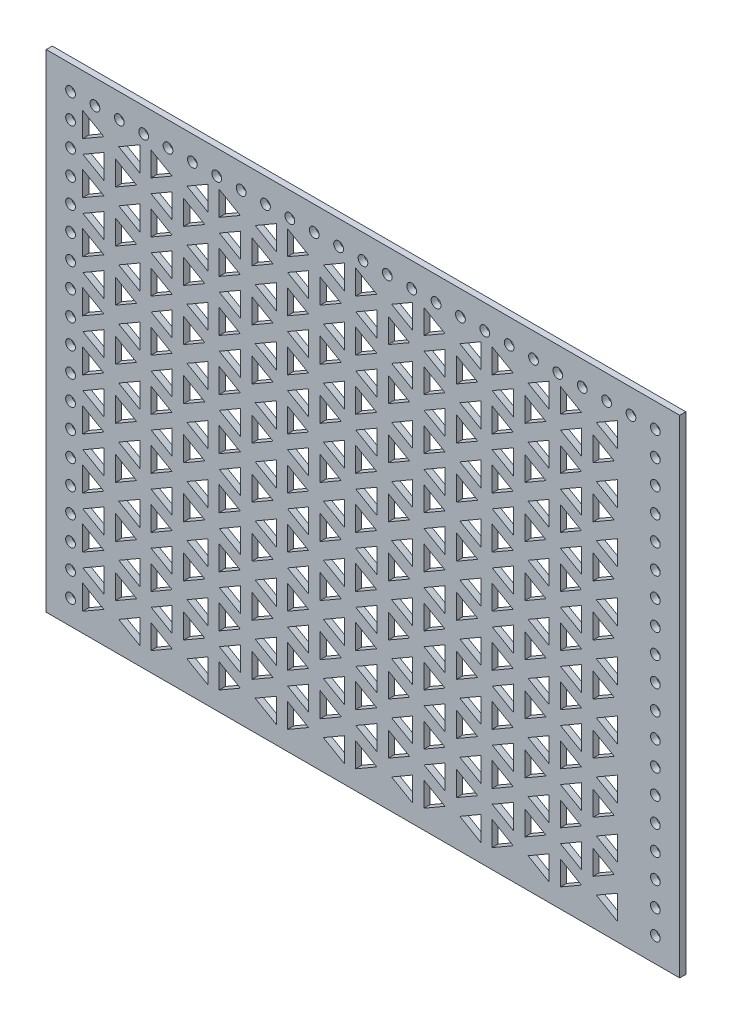
SolidWorks part; units mm, degrees
ref_plane "Front Plane" through (0, 0, 0) normal (0, 0, 1) x (1, 0, 0)
ref_plane "Top Plane" through (0, 0, 0) normal (0, 1, 0) x (1, 0, 0)
ref_plane "Right Plane" through (0, 0, 0) normal (1, 0, 0) x (0, 0, -1)
sketch "Sketch1" plane through (0, 0, 0) normal (0, 0, 1) x (1, 0, 0)
  line L1 (-91.9951, 64.6785) -> (238.2049, 64.6785)
  line L2 (-91.9951, 64.6785) -> (-91.9951, -189.3215)
  line L3 (-91.9951, -189.3215) -> (238.2049, -189.3215)
  line L4 (238.2049, 64.6785) -> (238.2049, -189.3215)
  line L15 (-61.9466, 40.3642) -> (-72.9451, 46.7142)
  line L16 (-72.9451, 46.7142) -> (-72.9451, 34.0142)
  line L17 (-72.9451, 34.0142) -> (-61.9466, 40.3642)
  line L18 (-61.8864, 20.5824) -> (-61.8864, 33.2824)
  line L19 (-61.8864, 33.2824) -> (-72.885, 26.9324)
  line L20 (-72.885, 26.9324) -> (-61.8864, 20.5824)
  line L25 (-44.876, 27.025) -> (-55.8745, 33.375)
  line L26 (-55.8745, 33.375) -> (-55.8745, 20.675)
  line L27 (-55.8745, 20.675) -> (-44.876, 27.025)
  line L28 (-43.2052, 33.3499) -> (-43.2052, 46.0499)
  line L29 (-43.2052, 46.0499) -> (-54.2037, 39.6999)
  line L30 (-54.2037, 39.6999) -> (-43.2052, 33.3499)
  line L31 (-26.3866, 40.3642) -> (-37.3851, 46.7142)
  line L32 (-37.3851, 46.7142) -> (-37.3851, 34.0142)
  line L33 (-37.3851, 34.0142) -> (-26.3866, 40.3642)
  line L34 (-26.3264, 20.5824) -> (-26.3264, 33.2824)
  line L35 (-26.3264, 33.2824) -> (-37.325, 26.9324)
  line L36 (-37.325, 26.9324) -> (-26.3264, 20.5824)
  line L37 (-9.316, 27.025) -> (-20.3145, 33.375)
  line L38 (-20.3145, 33.375) -> (-20.3145, 20.675)
  line L39 (-20.3145, 20.675) -> (-9.316, 27.025)
  line L40 (-7.6452, 33.3499) -> (-7.6452, 46.0499)
  line L41 (-7.6452, 46.0499) -> (-18.6437, 39.6999)
  line L42 (-18.6437, 39.6999) -> (-7.6452, 33.3499)
  line L43 (9.1734, 40.3642) -> (-1.8251, 46.7142)
  line L44 (-1.8251, 46.7142) -> (-1.8251, 34.0142)
  line L45 (-1.8251, 34.0142) -> (9.1734, 40.3642)
  line L46 (9.2336, 20.5824) -> (9.2336, 33.2824)
  line L47 (9.2336, 33.2824) -> (-1.765, 26.9324)
  line L48 (-1.765, 26.9324) -> (9.2336, 20.5824)
  line L49 (26.244, 27.025) -> (15.2455, 33.375)
  line L50 (15.2455, 33.375) -> (15.2455, 20.675)
  line L51 (15.2455, 20.675) -> (26.244, 27.025)
  line L52 (27.9148, 33.3499) -> (27.9148, 46.0499)
  line L53 (27.9148, 46.0499) -> (16.9163, 39.6999)
  line L54 (16.9163, 39.6999) -> (27.9148, 33.3499)
  line L55 (44.7334, 40.3642) -> (33.7349, 46.7142)
  line L56 (33.7349, 46.7142) -> (33.7349, 34.0142)
  line L57 (33.7349, 34.0142) -> (44.7334, 40.3642)
  line L58 (44.7936, 20.5824) -> (44.7936, 33.2824)
  line L59 (44.7936, 33.2824) -> (33.795, 26.9324)
  line L60 (33.795, 26.9324) -> (44.7936, 20.5824)
  line L61 (61.804, 27.025) -> (50.8055, 33.375)
  line L62 (50.8055, 33.375) -> (50.8055, 20.675)
  line L63 (50.8055, 20.675) -> (61.804, 27.025)
  line L64 (63.4748, 33.3499) -> (63.4748, 46.0499)
  line L65 (63.4748, 46.0499) -> (52.4763, 39.6999)
  line L66 (52.4763, 39.6999) -> (63.4748, 33.3499)
  line L67 (80.2934, 40.3642) -> (69.2949, 46.7142)
  line L68 (69.2949, 46.7142) -> (69.2949, 34.0142)
  line L69 (69.2949, 34.0142) -> (80.2934, 40.3642)
  line L70 (80.3536, 20.5824) -> (80.3536, 33.2824)
  line L71 (80.3536, 33.2824) -> (69.355, 26.9324)
  line L72 (69.355, 26.9324) -> (80.3536, 20.5824)
  line L73 (97.364, 27.025) -> (86.3655, 33.375)
  line L74 (86.3655, 33.375) -> (86.3655, 20.675)
  line L75 (86.3655, 20.675) -> (97.364, 27.025)
  line L76 (99.0348, 33.3499) -> (99.0348, 46.0499)
  line L77 (99.0348, 46.0499) -> (88.0363, 39.6999)
  line L78 (88.0363, 39.6999) -> (99.0348, 33.3499)
  line L79 (115.8534, 40.3642) -> (104.8549, 46.7142)
  line L80 (104.8549, 46.7142) -> (104.8549, 34.0142)
  line L81 (104.8549, 34.0142) -> (115.8534, 40.3642)
  line L82 (115.9136, 20.5824) -> (115.9136, 33.2824)
  line L83 (115.9136, 33.2824) -> (104.915, 26.9324)
  line L84 (104.915, 26.9324) -> (115.9136, 20.5824)
  line L85 (132.924, 27.025) -> (121.9255, 33.375)
  line L86 (121.9255, 33.375) -> (121.9255, 20.675)
  line L87 (121.9255, 20.675) -> (132.924, 27.025)
  line L88 (134.5948, 33.3499) -> (134.5948, 46.0499)
  line L89 (134.5948, 46.0499) -> (123.5963, 39.6999)
  line L90 (123.5963, 39.6999) -> (134.5948, 33.3499)
  line L91 (151.4134, 40.3642) -> (140.4149, 46.7142)
  line L92 (140.4149, 46.7142) -> (140.4149, 34.0142)
  line L93 (140.4149, 34.0142) -> (151.4134, 40.3642)
  line L94 (151.4736, 20.5824) -> (151.4736, 33.2824)
  line L95 (151.4736, 33.2824) -> (140.475, 26.9324)
  line L96 (140.475, 26.9324) -> (151.4736, 20.5824)
  line L97 (168.484, 27.025) -> (157.4855, 33.375)
  line L98 (157.4855, 33.375) -> (157.4855, 20.675)
  line L99 (157.4855, 20.675) -> (168.484, 27.025)
  line L100 (170.1548, 33.3499) -> (170.1548, 46.0499)
  line L101 (170.1548, 46.0499) -> (159.1563, 39.6999)
  line L102 (159.1563, 39.6999) -> (170.1548, 33.3499)
  line L103 (186.9734, 40.3642) -> (175.9749, 46.7142)
  line L104 (175.9749, 46.7142) -> (175.9749, 34.0142)
  line L105 (175.9749, 34.0142) -> (186.9734, 40.3642)
  line L106 (187.0336, 20.5824) -> (187.0336, 33.2824)
  line L107 (187.0336, 33.2824) -> (176.035, 26.9324)
  line L108 (176.035, 26.9324) -> (187.0336, 20.5824)
  line L109 (204.044, 27.025) -> (193.0455, 33.375)
  line L110 (193.0455, 33.375) -> (193.0455, 20.675)
  line L111 (193.0455, 20.675) -> (204.044, 27.025)
  line L112 (205.7148, 33.3499) -> (205.7148, 46.0499)
  line L113 (205.7148, 46.0499) -> (194.7163, 39.6999)
  line L114 (194.7163, 39.6999) -> (205.7148, 33.3499)
  line L115 (-26.3866, 13.6942) -> (-37.3851, 20.0442)
  line L116 (-37.3851, 20.0442) -> (-37.3851, 7.3442)
  line L117 (-37.3851, 7.3442) -> (-26.3866, 13.6942)
  line L118 (-26.3264, -6.0876) -> (-26.3264, 6.6124)
  line L119 (-26.3264, 6.6124) -> (-37.325, 0.2624)
  line L120 (-37.325, 0.2624) -> (-26.3264, -6.0876)
  line L121 (-9.316, 0.355) -> (-20.3145, 6.705)
  line L122 (-20.3145, 6.705) -> (-20.3145, -5.995)
  line L123 (-20.3145, -5.995) -> (-9.316, 0.355)
  line L124 (-7.6452, 6.6799) -> (-7.6452, 19.3799)
  line L125 (-7.6452, 19.3799) -> (-18.6437, 13.0299)
  line L126 (-18.6437, 13.0299) -> (-7.6452, 6.6799)
  line L127 (9.1734, 13.6942) -> (-1.8251, 20.0442)
  line L128 (-1.8251, 20.0442) -> (-1.8251, 7.3442)
  line L129 (-1.8251, 7.3442) -> (9.1734, 13.6942)
  line L130 (9.2336, -6.0876) -> (9.2336, 6.6124)
  line L131 (9.2336, 6.6124) -> (-1.765, 0.2624)
  line L132 (-1.765, 0.2624) -> (9.2336, -6.0876)
  line L133 (26.244, 0.355) -> (15.2455, 6.705)
  line L134 (15.2455, 6.705) -> (15.2455, -5.995)
  line L135 (15.2455, -5.995) -> (26.244, 0.355)
  line L136 (27.9148, 6.6799) -> (27.9148, 19.3799)
  line L137 (27.9148, 19.3799) -> (16.9163, 13.0299)
  line L138 (16.9163, 13.0299) -> (27.9148, 6.6799)
  line L139 (44.7334, 13.6942) -> (33.7349, 20.0442)
  line L140 (33.7349, 20.0442) -> (33.7349, 7.3442)
  line L141 (33.7349, 7.3442) -> (44.7334, 13.6942)
  line L142 (44.7936, -6.0876) -> (44.7936, 6.6124)
  line L143 (44.7936, 6.6124) -> (33.795, 0.2624)
  line L144 (33.795, 0.2624) -> (44.7936, -6.0876)
  line L145 (61.804, 0.355) -> (50.8055, 6.705)
  line L146 (50.8055, 6.705) -> (50.8055, -5.995)
  line L147 (50.8055, -5.995) -> (61.804, 0.355)
  line L148 (63.4748, 6.6799) -> (63.4748, 19.3799)
  line L149 (63.4748, 19.3799) -> (52.4763, 13.0299)
  line L150 (52.4763, 13.0299) -> (63.4748, 6.6799)
  line L151 (80.2934, 13.6942) -> (69.2949, 20.0442)
  line L152 (69.2949, 20.0442) -> (69.2949, 7.3442)
  line L153 (69.2949, 7.3442) -> (80.2934, 13.6942)
  line L154 (80.3536, -6.0876) -> (80.3536, 6.6124)
  line L155 (80.3536, 6.6124) -> (69.355, 0.2624)
  line L156 (69.355, 0.2624) -> (80.3536, -6.0876)
  line L157 (97.364, 0.355) -> (86.3655, 6.705)
  line L158 (86.3655, 6.705) -> (86.3655, -5.995)
  line L159 (86.3655, -5.995) -> (97.364, 0.355)
  line L160 (99.0348, 6.6799) -> (99.0348, 19.3799)
  line L161 (99.0348, 19.3799) -> (88.0363, 13.0299)
  line L162 (88.0363, 13.0299) -> (99.0348, 6.6799)
  line L163 (115.8534, 13.6942) -> (104.8549, 20.0442)
  line L164 (104.8549, 20.0442) -> (104.8549, 7.3442)
  line L165 (104.8549, 7.3442) -> (115.8534, 13.6942)
  line L166 (115.9136, -6.0876) -> (115.9136, 6.6124)
  line L167 (115.9136, 6.6124) -> (104.915, 0.2624)
  line L168 (104.915, 0.2624) -> (115.9136, -6.0876)
  line L169 (132.924, 0.355) -> (121.9255, 6.705)
  line L170 (121.9255, 6.705) -> (121.9255, -5.995)
  line L171 (121.9255, -5.995) -> (132.924, 0.355)
  line L172 (134.5948, 6.6799) -> (134.5948, 19.3799)
  line L173 (134.5948, 19.3799) -> (123.5963, 13.0299)
  line L174 (123.5963, 13.0299) -> (134.5948, 6.6799)
  line L175 (151.4134, 13.6942) -> (140.4149, 20.0442)
  line L176 (140.4149, 20.0442) -> (140.4149, 7.3442)
  line L177 (140.4149, 7.3442) -> (151.4134, 13.6942)
  line L178 (151.4736, -6.0876) -> (151.4736, 6.6124)
  line L179 (151.4736, 6.6124) -> (140.475, 0.2624)
  line L180 (140.475, 0.2624) -> (151.4736, -6.0876)
  line L181 (168.484, 0.355) -> (157.4855, 6.705)
  line L182 (157.4855, 6.705) -> (157.4855, -5.995)
  line L183 (157.4855, -5.995) -> (168.484, 0.355)
  line L184 (170.1548, 6.6799) -> (170.1548, 19.3799)
  line L185 (170.1548, 19.3799) -> (159.1563, 13.0299)
  line L186 (159.1563, 13.0299) -> (170.1548, 6.6799)
  line L187 (186.9734, 13.6942) -> (175.9749, 20.0442)
  line L188 (175.9749, 20.0442) -> (175.9749, 7.3442)
  line L189 (175.9749, 7.3442) -> (186.9734, 13.6942)
  line L190 (187.0336, -6.0876) -> (187.0336, 6.6124)
  line L191 (187.0336, 6.6124) -> (176.035, 0.2624)
  line L192 (176.035, 0.2624) -> (187.0336, -6.0876)
  line L193 (204.044, 0.355) -> (193.0455, 6.705)
  line L194 (193.0455, 6.705) -> (193.0455, -5.995)
  line L195 (193.0455, -5.995) -> (204.044, 0.355)
  line L196 (205.7148, 6.6799) -> (205.7148, 19.3799)
  line L197 (205.7148, 19.3799) -> (194.7163, 13.0299)
  line L198 (194.7163, 13.0299) -> (205.7148, 6.6799)
  line L199 (-26.3866, -12.9758) -> (-37.3851, -6.6258)
  line L200 (-37.3851, -6.6258) -> (-37.3851, -19.3258)
  line L201 (-37.3851, -19.3258) -> (-26.3866, -12.9758)
  line L202 (-26.3264, -32.7576) -> (-26.3264, -20.0576)
  line L203 (-26.3264, -20.0576) -> (-37.325, -26.4076)
  line L204 (-37.325, -26.4076) -> (-26.3264, -32.7576)
  line L205 (-9.316, -26.315) -> (-20.3145, -19.965)
  line L206 (-20.3145, -19.965) -> (-20.3145, -32.665)
  line L207 (-20.3145, -32.665) -> (-9.316, -26.315)
  line L208 (-7.6452, -19.9901) -> (-7.6452, -7.2901)
  line L209 (-7.6452, -7.2901) -> (-18.6437, -13.6401)
  line L210 (-18.6437, -13.6401) -> (-7.6452, -19.9901)
  line L211 (9.1734, -12.9758) -> (-1.8251, -6.6258)
  line L212 (-1.8251, -6.6258) -> (-1.8251, -19.3258)
  line L213 (-1.8251, -19.3258) -> (9.1734, -12.9758)
  line L214 (9.2336, -32.7576) -> (9.2336, -20.0576)
  line L215 (9.2336, -20.0576) -> (-1.765, -26.4076)
  line L216 (-1.765, -26.4076) -> (9.2336, -32.7576)
  line L217 (26.244, -26.315) -> (15.2455, -19.965)
  line L218 (15.2455, -19.965) -> (15.2455, -32.665)
  line L219 (15.2455, -32.665) -> (26.244, -26.315)
  line L220 (27.9148, -19.9901) -> (27.9148, -7.2901)
  line L221 (27.9148, -7.2901) -> (16.9163, -13.6401)
  line L222 (16.9163, -13.6401) -> (27.9148, -19.9901)
  line L223 (44.7334, -12.9758) -> (33.7349, -6.6258)
  line L224 (33.7349, -6.6258) -> (33.7349, -19.3258)
  line L225 (33.7349, -19.3258) -> (44.7334, -12.9758)
  line L226 (44.7936, -32.7576) -> (44.7936, -20.0576)
  line L227 (44.7936, -20.0576) -> (33.795, -26.4076)
  line L228 (33.795, -26.4076) -> (44.7936, -32.7576)
  line L229 (61.804, -26.315) -> (50.8055, -19.965)
  line L230 (50.8055, -19.965) -> (50.8055, -32.665)
  line L231 (50.8055, -32.665) -> (61.804, -26.315)
  line L232 (63.4748, -19.9901) -> (63.4748, -7.2901)
  line L233 (63.4748, -7.2901) -> (52.4763, -13.6401)
  line L234 (52.4763, -13.6401) -> (63.4748, -19.9901)
  line L235 (80.2934, -12.9758) -> (69.2949, -6.6258)
  line L236 (69.2949, -6.6258) -> (69.2949, -19.3258)
  line L237 (69.2949, -19.3258) -> (80.2934, -12.9758)
  line L238 (80.3536, -32.7576) -> (80.3536, -20.0576)
  line L239 (80.3536, -20.0576) -> (69.355, -26.4076)
  line L240 (69.355, -26.4076) -> (80.3536, -32.7576)
  line L241 (97.364, -26.315) -> (86.3655, -19.965)
  line L242 (86.3655, -19.965) -> (86.3655, -32.665)
  line L243 (86.3655, -32.665) -> (97.364, -26.315)
  line L244 (99.0348, -19.9901) -> (99.0348, -7.2901)
  line L245 (99.0348, -7.2901) -> (88.0363, -13.6401)
  line L246 (88.0363, -13.6401) -> (99.0348, -19.9901)
  line L247 (115.8534, -12.9758) -> (104.8549, -6.6258)
  line L248 (104.8549, -6.6258) -> (104.8549, -19.3258)
  line L249 (104.8549, -19.3258) -> (115.8534, -12.9758)
  line L250 (115.9136, -32.7576) -> (115.9136, -20.0576)
  line L251 (115.9136, -20.0576) -> (104.915, -26.4076)
  line L252 (104.915, -26.4076) -> (115.9136, -32.7576)
  line L253 (132.924, -26.315) -> (121.9255, -19.965)
  line L254 (121.9255, -19.965) -> (121.9255, -32.665)
  line L255 (121.9255, -32.665) -> (132.924, -26.315)
  line L256 (134.5948, -19.9901) -> (134.5948, -7.2901)
  line L257 (134.5948, -7.2901) -> (123.5963, -13.6401)
  line L258 (123.5963, -13.6401) -> (134.5948, -19.9901)
  line L259 (151.4134, -12.9758) -> (140.4149, -6.6258)
  line L260 (140.4149, -6.6258) -> (140.4149, -19.3258)
  line L261 (140.4149, -19.3258) -> (151.4134, -12.9758)
  line L262 (151.4736, -32.7576) -> (151.4736, -20.0576)
  line L263 (151.4736, -20.0576) -> (140.475, -26.4076)
  line L264 (140.475, -26.4076) -> (151.4736, -32.7576)
  line L265 (168.484, -26.315) -> (157.4855, -19.965)
  line L266 (157.4855, -19.965) -> (157.4855, -32.665)
  line L267 (157.4855, -32.665) -> (168.484, -26.315)
  line L268 (170.1548, -19.9901) -> (170.1548, -7.2901)
  line L269 (170.1548, -7.2901) -> (159.1563, -13.6401)
  line L270 (159.1563, -13.6401) -> (170.1548, -19.9901)
  line L271 (186.9734, -12.9758) -> (175.9749, -6.6258)
  line L272 (175.9749, -6.6258) -> (175.9749, -19.3258)
  line L273 (175.9749, -19.3258) -> (186.9734, -12.9758)
  line L274 (187.0336, -32.7576) -> (187.0336, -20.0576)
  line L275 (187.0336, -20.0576) -> (176.035, -26.4076)
  line L276 (176.035, -26.4076) -> (187.0336, -32.7576)
  line L277 (204.044, -26.315) -> (193.0455, -19.965)
  line L278 (193.0455, -19.965) -> (193.0455, -32.665)
  line L279 (193.0455, -32.665) -> (204.044, -26.315)
  line L280 (205.7148, -19.9901) -> (205.7148, -7.2901)
  line L281 (205.7148, -7.2901) -> (194.7163, -13.6401)
  line L282 (194.7163, -13.6401) -> (205.7148, -19.9901)
  line L283 (-26.3866, -39.6458) -> (-37.3851, -33.2958)
  line L284 (-37.3851, -33.2958) -> (-37.3851, -45.9958)
  line L285 (-37.3851, -45.9958) -> (-26.3866, -39.6458)
  line L286 (-26.3264, -59.4276) -> (-26.3264, -46.7276)
  line L287 (-26.3264, -46.7276) -> (-37.325, -53.0776)
  line L288 (-37.325, -53.0776) -> (-26.3264, -59.4276)
  line L289 (-9.316, -52.985) -> (-20.3145, -46.635)
  line L290 (-20.3145, -46.635) -> (-20.3145, -59.335)
  line L291 (-20.3145, -59.335) -> (-9.316, -52.985)
  line L292 (-7.6452, -46.6601) -> (-7.6452, -33.9601)
  line L293 (-7.6452, -33.9601) -> (-18.6437, -40.3101)
  line L294 (-18.6437, -40.3101) -> (-7.6452, -46.6601)
  line L295 (9.1734, -39.6458) -> (-1.8251, -33.2958)
  line L296 (-1.8251, -33.2958) -> (-1.8251, -45.9958)
  line L297 (-1.8251, -45.9958) -> (9.1734, -39.6458)
  line L298 (9.2336, -59.4276) -> (9.2336, -46.7276)
  line L299 (9.2336, -46.7276) -> (-1.765, -53.0776)
  line L300 (-1.765, -53.0776) -> (9.2336, -59.4276)
  line L301 (26.244, -52.985) -> (15.2455, -46.635)
  line L302 (15.2455, -46.635) -> (15.2455, -59.335)
  line L303 (15.2455, -59.335) -> (26.244, -52.985)
  line L304 (27.9148, -46.6601) -> (27.9148, -33.9601)
  line L305 (27.9148, -33.9601) -> (16.9163, -40.3101)
  line L306 (16.9163, -40.3101) -> (27.9148, -46.6601)
  line L307 (44.7334, -39.6458) -> (33.7349, -33.2958)
  line L308 (33.7349, -33.2958) -> (33.7349, -45.9958)
  line L309 (33.7349, -45.9958) -> (44.7334, -39.6458)
  line L310 (44.7936, -59.4276) -> (44.7936, -46.7276)
  line L311 (44.7936, -46.7276) -> (33.795, -53.0776)
  line L312 (33.795, -53.0776) -> (44.7936, -59.4276)
  line L313 (61.804, -52.985) -> (50.8055, -46.635)
  line L314 (50.8055, -46.635) -> (50.8055, -59.335)
  line L315 (50.8055, -59.335) -> (61.804, -52.985)
  line L316 (63.4748, -46.6601) -> (63.4748, -33.9601)
  line L317 (63.4748, -33.9601) -> (52.4763, -40.3101)
  line L318 (52.4763, -40.3101) -> (63.4748, -46.6601)
  line L319 (80.2934, -39.6458) -> (69.2949, -33.2958)
  line L320 (69.2949, -33.2958) -> (69.2949, -45.9958)
  line L321 (69.2949, -45.9958) -> (80.2934, -39.6458)
  line L322 (80.3536, -59.4276) -> (80.3536, -46.7276)
  line L323 (80.3536, -46.7276) -> (69.355, -53.0776)
  line L324 (69.355, -53.0776) -> (80.3536, -59.4276)
  line L325 (97.364, -52.985) -> (86.3655, -46.635)
  line L326 (86.3655, -46.635) -> (86.3655, -59.335)
  line L327 (86.3655, -59.335) -> (97.364, -52.985)
  line L328 (99.0348, -46.6601) -> (99.0348, -33.9601)
  line L329 (99.0348, -33.9601) -> (88.0363, -40.3101)
  line L330 (88.0363, -40.3101) -> (99.0348, -46.6601)
  line L331 (115.8534, -39.6458) -> (104.8549, -33.2958)
  line L332 (104.8549, -33.2958) -> (104.8549, -45.9958)
  line L333 (104.8549, -45.9958) -> (115.8534, -39.6458)
  line L334 (115.9136, -59.4276) -> (115.9136, -46.7276)
  line L335 (115.9136, -46.7276) -> (104.915, -53.0776)
  line L336 (104.915, -53.0776) -> (115.9136, -59.4276)
  line L337 (132.924, -52.985) -> (121.9255, -46.635)
  line L338 (121.9255, -46.635) -> (121.9255, -59.335)
  line L339 (121.9255, -59.335) -> (132.924, -52.985)
  line L340 (134.5948, -46.6601) -> (134.5948, -33.9601)
  line L341 (134.5948, -33.9601) -> (123.5963, -40.3101)
  line L342 (123.5963, -40.3101) -> (134.5948, -46.6601)
  line L343 (151.4134, -39.6458) -> (140.4149, -33.2958)
  line L344 (140.4149, -33.2958) -> (140.4149, -45.9958)
  line L345 (140.4149, -45.9958) -> (151.4134, -39.6458)
  line L346 (151.4736, -59.4276) -> (151.4736, -46.7276)
  line L347 (151.4736, -46.7276) -> (140.475, -53.0776)
  line L348 (140.475, -53.0776) -> (151.4736, -59.4276)
  line L349 (168.484, -52.985) -> (157.4855, -46.635)
  line L350 (157.4855, -46.635) -> (157.4855, -59.335)
  line L351 (157.4855, -59.335) -> (168.484, -52.985)
  line L352 (170.1548, -46.6601) -> (170.1548, -33.9601)
  line L353 (170.1548, -33.9601) -> (159.1563, -40.3101)
  line L354 (159.1563, -40.3101) -> (170.1548, -46.6601)
  line L355 (186.9734, -39.6458) -> (175.9749, -33.2958)
  line L356 (175.9749, -33.2958) -> (175.9749, -45.9958)
  line L357 (175.9749, -45.9958) -> (186.9734, -39.6458)
  line L358 (187.0336, -59.4276) -> (187.0336, -46.7276)
  line L359 (187.0336, -46.7276) -> (176.035, -53.0776)
  line L360 (176.035, -53.0776) -> (187.0336, -59.4276)
  line L361 (204.044, -52.985) -> (193.0455, -46.635)
  line L362 (193.0455, -46.635) -> (193.0455, -59.335)
  line L363 (193.0455, -59.335) -> (204.044, -52.985)
  line L364 (205.7148, -46.6601) -> (205.7148, -33.9601)
  line L365 (205.7148, -33.9601) -> (194.7163, -40.3101)
  line L366 (194.7163, -40.3101) -> (205.7148, -46.6601)
  line L367 (-26.3866, -66.3158) -> (-37.3851, -59.9658)
  line L368 (-37.3851, -59.9658) -> (-37.3851, -72.6658)
  line L369 (-37.3851, -72.6658) -> (-26.3866, -66.3158)
  line L370 (-26.3264, -86.0976) -> (-26.3264, -73.3976)
  line L371 (-26.3264, -73.3976) -> (-37.325, -79.7476)
  line L372 (-37.325, -79.7476) -> (-26.3264, -86.0976)
  line L373 (-9.316, -79.655) -> (-20.3145, -73.305)
  line L374 (-20.3145, -73.305) -> (-20.3145, -86.005)
  line L375 (-20.3145, -86.005) -> (-9.316, -79.655)
  line L376 (-7.6452, -73.3301) -> (-7.6452, -60.6301)
  line L377 (-7.6452, -60.6301) -> (-18.6437, -66.9801)
  line L378 (-18.6437, -66.9801) -> (-7.6452, -73.3301)
  line L379 (9.1734, -66.3158) -> (-1.8251, -59.9658)
  line L380 (-1.8251, -59.9658) -> (-1.8251, -72.6658)
  line L381 (-1.8251, -72.6658) -> (9.1734, -66.3158)
  line L382 (9.2336, -86.0976) -> (9.2336, -73.3976)
  line L383 (9.2336, -73.3976) -> (-1.765, -79.7476)
  line L384 (-1.765, -79.7476) -> (9.2336, -86.0976)
  line L385 (26.244, -79.655) -> (15.2455, -73.305)
  line L386 (15.2455, -73.305) -> (15.2455, -86.005)
  line L387 (15.2455, -86.005) -> (26.244, -79.655)
  line L388 (27.9148, -73.3301) -> (27.9148, -60.6301)
  line L389 (27.9148, -60.6301) -> (16.9163, -66.9801)
  line L390 (16.9163, -66.9801) -> (27.9148, -73.3301)
  line L391 (44.7334, -66.3158) -> (33.7349, -59.9658)
  line L392 (33.7349, -59.9658) -> (33.7349, -72.6658)
  line L393 (33.7349, -72.6658) -> (44.7334, -66.3158)
  line L394 (44.7936, -86.0976) -> (44.7936, -73.3976)
  line L395 (44.7936, -73.3976) -> (33.795, -79.7476)
  line L396 (33.795, -79.7476) -> (44.7936, -86.0976)
  line L397 (61.804, -79.655) -> (50.8055, -73.305)
  line L398 (50.8055, -73.305) -> (50.8055, -86.005)
  line L399 (50.8055, -86.005) -> (61.804, -79.655)
  line L400 (63.4748, -73.3301) -> (63.4748, -60.6301)
  line L401 (63.4748, -60.6301) -> (52.4763, -66.9801)
  line L402 (52.4763, -66.9801) -> (63.4748, -73.3301)
  line L403 (80.2934, -66.3158) -> (69.2949, -59.9658)
  line L404 (69.2949, -59.9658) -> (69.2949, -72.6658)
  line L405 (69.2949, -72.6658) -> (80.2934, -66.3158)
  line L406 (80.3536, -86.0976) -> (80.3536, -73.3976)
  line L407 (80.3536, -73.3976) -> (69.355, -79.7476)
  line L408 (69.355, -79.7476) -> (80.3536, -86.0976)
  line L409 (97.364, -79.655) -> (86.3655, -73.305)
  line L410 (86.3655, -73.305) -> (86.3655, -86.005)
  line L411 (86.3655, -86.005) -> (97.364, -79.655)
  line L412 (99.0348, -73.3301) -> (99.0348, -60.6301)
  line L413 (99.0348, -60.6301) -> (88.0363, -66.9801)
  line L414 (88.0363, -66.9801) -> (99.0348, -73.3301)
  line L415 (115.8534, -66.3158) -> (104.8549, -59.9658)
  line L416 (104.8549, -59.9658) -> (104.8549, -72.6658)
  line L417 (104.8549, -72.6658) -> (115.8534, -66.3158)
  line L418 (115.9136, -86.0976) -> (115.9136, -73.3976)
  line L419 (115.9136, -73.3976) -> (104.915, -79.7476)
  line L420 (104.915, -79.7476) -> (115.9136, -86.0976)
  line L421 (132.924, -79.655) -> (121.9255, -73.305)
  line L422 (121.9255, -73.305) -> (121.9255, -86.005)
  line L423 (121.9255, -86.005) -> (132.924, -79.655)
  line L424 (134.5948, -73.3301) -> (134.5948, -60.6301)
  line L425 (134.5948, -60.6301) -> (123.5963, -66.9801)
  line L426 (123.5963, -66.9801) -> (134.5948, -73.3301)
  line L427 (151.4134, -66.3158) -> (140.4149, -59.9658)
  line L428 (140.4149, -59.9658) -> (140.4149, -72.6658)
  line L429 (140.4149, -72.6658) -> (151.4134, -66.3158)
  line L430 (151.4736, -86.0976) -> (151.4736, -73.3976)
  line L431 (151.4736, -73.3976) -> (140.475, -79.7476)
  line L432 (140.475, -79.7476) -> (151.4736, -86.0976)
  line L433 (168.484, -79.655) -> (157.4855, -73.305)
  line L434 (157.4855, -73.305) -> (157.4855, -86.005)
  line L435 (157.4855, -86.005) -> (168.484, -79.655)
  line L436 (170.1548, -73.3301) -> (170.1548, -60.6301)
  line L437 (170.1548, -60.6301) -> (159.1563, -66.9801)
  line L438 (159.1563, -66.9801) -> (170.1548, -73.3301)
  line L439 (186.9734, -66.3158) -> (175.9749, -59.9658)
  line L440 (175.9749, -59.9658) -> (175.9749, -72.6658)
  line L441 (175.9749, -72.6658) -> (186.9734, -66.3158)
  line L442 (187.0336, -86.0976) -> (187.0336, -73.3976)
  line L443 (187.0336, -73.3976) -> (176.035, -79.7476)
  line L444 (176.035, -79.7476) -> (187.0336, -86.0976)
  line L445 (204.044, -79.655) -> (193.0455, -73.305)
  line L446 (193.0455, -73.305) -> (193.0455, -86.005)
  line L447 (193.0455, -86.005) -> (204.044, -79.655)
  line L448 (205.7148, -73.3301) -> (205.7148, -60.6301)
  line L449 (205.7148, -60.6301) -> (194.7163, -66.9801)
  line L450 (194.7163, -66.9801) -> (205.7148, -73.3301)
  line L451 (-26.3866, -92.9858) -> (-37.3851, -86.6358)
  line L452 (-37.3851, -86.6358) -> (-37.3851, -99.3358)
  line L453 (-37.3851, -99.3358) -> (-26.3866, -92.9858)
  line L454 (-26.3264, -112.7676) -> (-26.3264, -100.0676)
  line L455 (-26.3264, -100.0676) -> (-37.325, -106.4176)
  line L456 (-37.325, -106.4176) -> (-26.3264, -112.7676)
  line L457 (-9.316, -106.325) -> (-20.3145, -99.975)
  line L458 (-20.3145, -99.975) -> (-20.3145, -112.675)
  line L459 (-20.3145, -112.675) -> (-9.316, -106.325)
  line L460 (-7.6452, -100.0001) -> (-7.6452, -87.3001)
  line L461 (-7.6452, -87.3001) -> (-18.6437, -93.6501)
  line L462 (-18.6437, -93.6501) -> (-7.6452, -100.0001)
  line L463 (9.1734, -92.9858) -> (-1.8251, -86.6358)
  line L464 (-1.8251, -86.6358) -> (-1.8251, -99.3358)
  line L465 (-1.8251, -99.3358) -> (9.1734, -92.9858)
  line L466 (9.2336, -112.7676) -> (9.2336, -100.0676)
  line L467 (9.2336, -100.0676) -> (-1.765, -106.4176)
  line L468 (-1.765, -106.4176) -> (9.2336, -112.7676)
  line L469 (26.244, -106.325) -> (15.2455, -99.975)
  line L470 (15.2455, -99.975) -> (15.2455, -112.675)
  line L471 (15.2455, -112.675) -> (26.244, -106.325)
  line L472 (27.9148, -100.0001) -> (27.9148, -87.3001)
  line L473 (27.9148, -87.3001) -> (16.9163, -93.6501)
  line L474 (16.9163, -93.6501) -> (27.9148, -100.0001)
  line L475 (44.7334, -92.9858) -> (33.7349, -86.6358)
  line L476 (33.7349, -86.6358) -> (33.7349, -99.3358)
  line L477 (33.7349, -99.3358) -> (44.7334, -92.9858)
  line L478 (44.7936, -112.7676) -> (44.7936, -100.0676)
  line L479 (44.7936, -100.0676) -> (33.795, -106.4176)
  line L480 (33.795, -106.4176) -> (44.7936, -112.7676)
  line L481 (61.804, -106.325) -> (50.8055, -99.975)
  line L482 (50.8055, -99.975) -> (50.8055, -112.675)
  line L483 (50.8055, -112.675) -> (61.804, -106.325)
  line L484 (63.4748, -100.0001) -> (63.4748, -87.3001)
  line L485 (63.4748, -87.3001) -> (52.4763, -93.6501)
  line L486 (52.4763, -93.6501) -> (63.4748, -100.0001)
  line L487 (80.2934, -92.9858) -> (69.2949, -86.6358)
  line L488 (69.2949, -86.6358) -> (69.2949, -99.3358)
  line L489 (69.2949, -99.3358) -> (80.2934, -92.9858)
  line L490 (80.3536, -112.7676) -> (80.3536, -100.0676)
  line L491 (80.3536, -100.0676) -> (69.355, -106.4176)
  line L492 (69.355, -106.4176) -> (80.3536, -112.7676)
  line L493 (97.364, -106.325) -> (86.3655, -99.975)
  line L494 (86.3655, -99.975) -> (86.3655, -112.675)
  line L495 (86.3655, -112.675) -> (97.364, -106.325)
  line L496 (99.0348, -100.0001) -> (99.0348, -87.3001)
  line L497 (99.0348, -87.3001) -> (88.0363, -93.6501)
  line L498 (88.0363, -93.6501) -> (99.0348, -100.0001)
  line L499 (115.8534, -92.9858) -> (104.8549, -86.6358)
  line L500 (104.8549, -86.6358) -> (104.8549, -99.3358)
  line L501 (104.8549, -99.3358) -> (115.8534, -92.9858)
  line L502 (115.9136, -112.7676) -> (115.9136, -100.0676)
  line L503 (115.9136, -100.0676) -> (104.915, -106.4176)
  line L504 (104.915, -106.4176) -> (115.9136, -112.7676)
  line L505 (132.924, -106.325) -> (121.9255, -99.975)
  line L506 (121.9255, -99.975) -> (121.9255, -112.675)
  line L507 (121.9255, -112.675) -> (132.924, -106.325)
  line L508 (134.5948, -100.0001) -> (134.5948, -87.3001)
  line L509 (134.5948, -87.3001) -> (123.5963, -93.6501)
  line L510 (123.5963, -93.6501) -> (134.5948, -100.0001)
  line L511 (151.4134, -92.9858) -> (140.4149, -86.6358)
  line L512 (140.4149, -86.6358) -> (140.4149, -99.3358)
  line L513 (140.4149, -99.3358) -> (151.4134, -92.9858)
  line L514 (151.4736, -112.7676) -> (151.4736, -100.0676)
  line L515 (151.4736, -100.0676) -> (140.475, -106.4176)
  line L516 (140.475, -106.4176) -> (151.4736, -112.7676)
  line L517 (168.484, -106.325) -> (157.4855, -99.975)
  line L518 (157.4855, -99.975) -> (157.4855, -112.675)
  line L519 (157.4855, -112.675) -> (168.484, -106.325)
  line L520 (170.1548, -100.0001) -> (170.1548, -87.3001)
  line L521 (170.1548, -87.3001) -> (159.1563, -93.6501)
  line L522 (159.1563, -93.6501) -> (170.1548, -100.0001)
  line L523 (186.9734, -92.9858) -> (175.9749, -86.6358)
  line L524 (175.9749, -86.6358) -> (175.9749, -99.3358)
  line L525 (175.9749, -99.3358) -> (186.9734, -92.9858)
  line L526 (187.0336, -112.7676) -> (187.0336, -100.0676)
  line L527 (187.0336, -100.0676) -> (176.035, -106.4176)
  line L528 (176.035, -106.4176) -> (187.0336, -112.7676)
  line L529 (204.044, -106.325) -> (193.0455, -99.975)
  line L530 (193.0455, -99.975) -> (193.0455, -112.675)
  line L531 (193.0455, -112.675) -> (204.044, -106.325)
  line L532 (205.7148, -100.0001) -> (205.7148, -87.3001)
  line L533 (205.7148, -87.3001) -> (194.7163, -93.6501)
  line L534 (194.7163, -93.6501) -> (205.7148, -100.0001)
  line L535 (-26.3866, -119.6558) -> (-37.3851, -113.3058)
  line L536 (-37.3851, -113.3058) -> (-37.3851, -126.0058)
  line L537 (-37.3851, -126.0058) -> (-26.3866, -119.6558)
  line L538 (-26.3264, -139.4376) -> (-26.3264, -126.7376)
  line L539 (-26.3264, -126.7376) -> (-37.325, -133.0876)
  line L540 (-37.325, -133.0876) -> (-26.3264, -139.4376)
  line L541 (-9.316, -132.995) -> (-20.3145, -126.645)
  line L542 (-20.3145, -126.645) -> (-20.3145, -139.345)
  line L543 (-20.3145, -139.345) -> (-9.316, -132.995)
  line L544 (-7.6452, -126.6701) -> (-7.6452, -113.9701)
  line L545 (-7.6452, -113.9701) -> (-18.6437, -120.3201)
  line L546 (-18.6437, -120.3201) -> (-7.6452, -126.6701)
  line L547 (9.1734, -119.6558) -> (-1.8251, -113.3058)
  line L548 (-1.8251, -113.3058) -> (-1.8251, -126.0058)
  line L549 (-1.8251, -126.0058) -> (9.1734, -119.6558)
  line L550 (9.2336, -139.4376) -> (9.2336, -126.7376)
  line L551 (9.2336, -126.7376) -> (-1.765, -133.0876)
  line L552 (-1.765, -133.0876) -> (9.2336, -139.4376)
  line L553 (26.244, -132.995) -> (15.2455, -126.645)
  line L554 (15.2455, -126.645) -> (15.2455, -139.345)
  line L555 (15.2455, -139.345) -> (26.244, -132.995)
  line L556 (27.9148, -126.6701) -> (27.9148, -113.9701)
  line L557 (27.9148, -113.9701) -> (16.9163, -120.3201)
  line L558 (16.9163, -120.3201) -> (27.9148, -126.6701)
  line L559 (44.7334, -119.6558) -> (33.7349, -113.3058)
  line L560 (33.7349, -113.3058) -> (33.7349, -126.0058)
  line L561 (33.7349, -126.0058) -> (44.7334, -119.6558)
  line L562 (44.7936, -139.4376) -> (44.7936, -126.7376)
  line L563 (44.7936, -126.7376) -> (33.795, -133.0876)
  line L564 (33.795, -133.0876) -> (44.7936, -139.4376)
  line L565 (61.804, -132.995) -> (50.8055, -126.645)
  line L566 (50.8055, -126.645) -> (50.8055, -139.345)
  line L567 (50.8055, -139.345) -> (61.804, -132.995)
  line L568 (63.4748, -126.6701) -> (63.4748, -113.9701)
  line L569 (63.4748, -113.9701) -> (52.4763, -120.3201)
  line L570 (52.4763, -120.3201) -> (63.4748, -126.6701)
  line L571 (80.2934, -119.6558) -> (69.2949, -113.3058)
  line L572 (69.2949, -113.3058) -> (69.2949, -126.0058)
  line L573 (69.2949, -126.0058) -> (80.2934, -119.6558)
  line L574 (80.3536, -139.4376) -> (80.3536, -126.7376)
  line L575 (80.3536, -126.7376) -> (69.355, -133.0876)
  line L576 (69.355, -133.0876) -> (80.3536, -139.4376)
  line L577 (97.364, -132.995) -> (86.3655, -126.645)
  line L578 (86.3655, -126.645) -> (86.3655, -139.345)
  line L579 (86.3655, -139.345) -> (97.364, -132.995)
  line L580 (99.0348, -126.6701) -> (99.0348, -113.9701)
  line L581 (99.0348, -113.9701) -> (88.0363, -120.3201)
  line L582 (88.0363, -120.3201) -> (99.0348, -126.6701)
  line L583 (115.8534, -119.6558) -> (104.8549, -113.3058)
  line L584 (104.8549, -113.3058) -> (104.8549, -126.0058)
  line L585 (104.8549, -126.0058) -> (115.8534, -119.6558)
  line L586 (115.9136, -139.4376) -> (115.9136, -126.7376)
  line L587 (115.9136, -126.7376) -> (104.915, -133.0876)
  line L588 (104.915, -133.0876) -> (115.9136, -139.4376)
  line L589 (132.924, -132.995) -> (121.9255, -126.645)
  line L590 (121.9255, -126.645) -> (121.9255, -139.345)
  line L591 (121.9255, -139.345) -> (132.924, -132.995)
  line L592 (134.5948, -126.6701) -> (134.5948, -113.9701)
  line L593 (134.5948, -113.9701) -> (123.5963, -120.3201)
  line L594 (123.5963, -120.3201) -> (134.5948, -126.6701)
  line L595 (151.4134, -119.6558) -> (140.4149, -113.3058)
  line L596 (140.4149, -113.3058) -> (140.4149, -126.0058)
  line L597 (140.4149, -126.0058) -> (151.4134, -119.6558)
  line L598 (151.4736, -139.4376) -> (151.4736, -126.7376)
  line L599 (151.4736, -126.7376) -> (140.475, -133.0876)
  line L600 (140.475, -133.0876) -> (151.4736, -139.4376)
  line L601 (168.484, -132.995) -> (157.4855, -126.645)
  line L602 (157.4855, -126.645) -> (157.4855, -139.345)
  line L603 (157.4855, -139.345) -> (168.484, -132.995)
  line L604 (170.1548, -126.6701) -> (170.1548, -113.9701)
  line L605 (170.1548, -113.9701) -> (159.1563, -120.3201)
  line L606 (159.1563, -120.3201) -> (170.1548, -126.6701)
  line L607 (186.9734, -119.6558) -> (175.9749, -113.3058)
  line L608 (175.9749, -113.3058) -> (175.9749, -126.0058)
  line L609 (175.9749, -126.0058) -> (186.9734, -119.6558)
  line L610 (187.0336, -139.4376) -> (187.0336, -126.7376)
  line L611 (187.0336, -126.7376) -> (176.035, -133.0876)
  line L612 (176.035, -133.0876) -> (187.0336, -139.4376)
  line L613 (204.044, -132.995) -> (193.0455, -126.645)
  line L614 (193.0455, -126.645) -> (193.0455, -139.345)
  line L615 (193.0455, -139.345) -> (204.044, -132.995)
  line L616 (205.7148, -126.6701) -> (205.7148, -113.9701)
  line L617 (205.7148, -113.9701) -> (194.7163, -120.3201)
  line L618 (194.7163, -120.3201) -> (205.7148, -126.6701)
  line L619 (-26.3866, -146.3258) -> (-37.3851, -139.9758)
  line L620 (-37.3851, -139.9758) -> (-37.3851, -152.6758)
  line L621 (-37.3851, -152.6758) -> (-26.3866, -146.3258)
  line L622 (-26.3264, -166.1076) -> (-26.3264, -153.4076)
  line L623 (-26.3264, -153.4076) -> (-37.325, -159.7576)
  line L624 (-37.325, -159.7576) -> (-26.3264, -166.1076)
  line L625 (-9.316, -159.665) -> (-20.3145, -153.315)
  line L626 (-20.3145, -153.315) -> (-20.3145, -166.015)
  line L627 (-20.3145, -166.015) -> (-9.316, -159.665)
  line L628 (-7.6452, -153.3401) -> (-7.6452, -140.6401)
  line L629 (-7.6452, -140.6401) -> (-18.6437, -146.9901)
  line L630 (-18.6437, -146.9901) -> (-7.6452, -153.3401)
  line L631 (9.1734, -146.3258) -> (-1.8251, -139.9758)
  line L632 (-1.8251, -139.9758) -> (-1.8251, -152.6758)
  line L633 (-1.8251, -152.6758) -> (9.1734, -146.3258)
  line L634 (9.2336, -166.1076) -> (9.2336, -153.4076)
  line L635 (9.2336, -153.4076) -> (-1.765, -159.7576)
  line L636 (-1.765, -159.7576) -> (9.2336, -166.1076)
  line L637 (26.244, -159.665) -> (15.2455, -153.315)
  line L638 (15.2455, -153.315) -> (15.2455, -166.015)
  line L639 (15.2455, -166.015) -> (26.244, -159.665)
  line L640 (27.9148, -153.3401) -> (27.9148, -140.6401)
  line L641 (27.9148, -140.6401) -> (16.9163, -146.9901)
  line L642 (16.9163, -146.9901) -> (27.9148, -153.3401)
  line L643 (44.7334, -146.3258) -> (33.7349, -139.9758)
  line L644 (33.7349, -139.9758) -> (33.7349, -152.6758)
  line L645 (33.7349, -152.6758) -> (44.7334, -146.3258)
  line L646 (44.7936, -166.1076) -> (44.7936, -153.4076)
  line L647 (44.7936, -153.4076) -> (33.795, -159.7576)
  line L648 (33.795, -159.7576) -> (44.7936, -166.1076)
  line L649 (61.804, -159.665) -> (50.8055, -153.315)
  line L650 (50.8055, -153.315) -> (50.8055, -166.015)
  line L651 (50.8055, -166.015) -> (61.804, -159.665)
  line L652 (63.4748, -153.3401) -> (63.4748, -140.6401)
  line L653 (63.4748, -140.6401) -> (52.4763, -146.9901)
  line L654 (52.4763, -146.9901) -> (63.4748, -153.3401)
  line L655 (80.2934, -146.3258) -> (69.2949, -139.9758)
  line L656 (69.2949, -139.9758) -> (69.2949, -152.6758)
  line L657 (69.2949, -152.6758) -> (80.2934, -146.3258)
  line L658 (80.3536, -166.1076) -> (80.3536, -153.4076)
  line L659 (80.3536, -153.4076) -> (69.355, -159.7576)
  line L660 (69.355, -159.7576) -> (80.3536, -166.1076)
  line L661 (97.364, -159.665) -> (86.3655, -153.315)
  line L662 (86.3655, -153.315) -> (86.3655, -166.015)
  line L663 (86.3655, -166.015) -> (97.364, -159.665)
  line L664 (99.0348, -153.3401) -> (99.0348, -140.6401)
  line L665 (99.0348, -140.6401) -> (88.0363, -146.9901)
  line L666 (88.0363, -146.9901) -> (99.0348, -153.3401)
  line L667 (115.8534, -146.3258) -> (104.8549, -139.9758)
  line L668 (104.8549, -139.9758) -> (104.8549, -152.6758)
  line L669 (104.8549, -152.6758) -> (115.8534, -146.3258)
  line L670 (115.9136, -166.1076) -> (115.9136, -153.4076)
  line L671 (115.9136, -153.4076) -> (104.915, -159.7576)
  line L672 (104.915, -159.7576) -> (115.9136, -166.1076)
  line L673 (132.924, -159.665) -> (121.9255, -153.315)
  line L674 (121.9255, -153.315) -> (121.9255, -166.015)
  line L675 (121.9255, -166.015) -> (132.924, -159.665)
  line L676 (134.5948, -153.3401) -> (134.5948, -140.6401)
  line L677 (134.5948, -140.6401) -> (123.5963, -146.9901)
  line L678 (123.5963, -146.9901) -> (134.5948, -153.3401)
  line L679 (151.4134, -146.3258) -> (140.4149, -139.9758)
  line L680 (140.4149, -139.9758) -> (140.4149, -152.6758)
  line L681 (140.4149, -152.6758) -> (151.4134, -146.3258)
  line L682 (151.4736, -166.1076) -> (151.4736, -153.4076)
  line L683 (151.4736, -153.4076) -> (140.475, -159.7576)
  line L684 (140.475, -159.7576) -> (151.4736, -166.1076)
  line L685 (168.484, -159.665) -> (157.4855, -153.315)
  line L686 (157.4855, -153.315) -> (157.4855, -166.015)
  line L687 (157.4855, -166.015) -> (168.484, -159.665)
  line L688 (170.1548, -153.3401) -> (170.1548, -140.6401)
  line L689 (170.1548, -140.6401) -> (159.1563, -146.9901)
  line L690 (159.1563, -146.9901) -> (170.1548, -153.3401)
  line L691 (186.9734, -146.3258) -> (175.9749, -139.9758)
  line L692 (175.9749, -139.9758) -> (175.9749, -152.6758)
  line L693 (175.9749, -152.6758) -> (186.9734, -146.3258)
  line L694 (187.0336, -166.1076) -> (187.0336, -153.4076)
  line L695 (187.0336, -153.4076) -> (176.035, -159.7576)
  line L696 (176.035, -159.7576) -> (187.0336, -166.1076)
  line L697 (204.044, -159.665) -> (193.0455, -153.315)
  line L698 (193.0455, -153.315) -> (193.0455, -166.015)
  line L699 (193.0455, -166.015) -> (204.044, -159.665)
  line L700 (205.7148, -153.3401) -> (205.7148, -140.6401)
  line L701 (205.7148, -140.6401) -> (194.7163, -146.9901)
  line L702 (194.7163, -146.9901) -> (205.7148, -153.3401)
  line L703 (-26.3866, -172.9958) -> (-37.3851, -166.6458)
  line L704 (-37.3851, -166.6458) -> (-37.3851, -179.3458)
  line L705 (-37.3851, -179.3458) -> (-26.3866, -172.9958)
  line L712 (-7.6452, -180.0101) -> (-7.6452, -167.3101)
  line L713 (-7.6452, -167.3101) -> (-18.6437, -173.6601)
  line L714 (-18.6437, -173.6601) -> (-7.6452, -180.0101)
  line L715 (9.1734, -172.9958) -> (-1.8251, -166.6458)
  line L716 (-1.8251, -166.6458) -> (-1.8251, -179.3458)
  line L717 (-1.8251, -179.3458) -> (9.1734, -172.9958)
  line L724 (27.9148, -180.0101) -> (27.9148, -167.3101)
  line L725 (27.9148, -167.3101) -> (16.9163, -173.6601)
  line L726 (16.9163, -173.6601) -> (27.9148, -180.0101)
  line L727 (44.7334, -172.9958) -> (33.7349, -166.6458)
  line L728 (33.7349, -166.6458) -> (33.7349, -179.3458)
  line L729 (33.7349, -179.3458) -> (44.7334, -172.9958)
  line L736 (63.4748, -180.0101) -> (63.4748, -167.3101)
  line L737 (63.4748, -167.3101) -> (52.4763, -173.6601)
  line L738 (52.4763, -173.6601) -> (63.4748, -180.0101)
  line L739 (80.2934, -172.9958) -> (69.2949, -166.6458)
  line L740 (69.2949, -166.6458) -> (69.2949, -179.3458)
  line L741 (69.2949, -179.3458) -> (80.2934, -172.9958)
  line L748 (99.0348, -180.0101) -> (99.0348, -167.3101)
  line L749 (99.0348, -167.3101) -> (88.0363, -173.6601)
  line L750 (88.0363, -173.6601) -> (99.0348, -180.0101)
  line L751 (115.8534, -172.9958) -> (104.8549, -166.6458)
  line L752 (104.8549, -166.6458) -> (104.8549, -179.3458)
  line L753 (104.8549, -179.3458) -> (115.8534, -172.9958)
  line L760 (134.5948, -180.0101) -> (134.5948, -167.3101)
  line L761 (134.5948, -167.3101) -> (123.5963, -173.6601)
  line L762 (123.5963, -173.6601) -> (134.5948, -180.0101)
  line L763 (151.4134, -172.9958) -> (140.4149, -166.6458)
  line L764 (140.4149, -166.6458) -> (140.4149, -179.3458)
  line L765 (140.4149, -179.3458) -> (151.4134, -172.9958)
  line L772 (170.1548, -180.0101) -> (170.1548, -167.3101)
  line L773 (170.1548, -167.3101) -> (159.1563, -173.6601)
  line L774 (159.1563, -173.6601) -> (170.1548, -180.0101)
  line L775 (186.9734, -172.9958) -> (175.9749, -166.6458)
  line L776 (175.9749, -166.6458) -> (175.9749, -179.3458)
  line L777 (175.9749, -179.3458) -> (186.9734, -172.9958)
  line L784 (205.7148, -180.0101) -> (205.7148, -167.3101)
  line L785 (205.7148, -167.3101) -> (194.7163, -173.6601)
  line L786 (194.7163, -173.6601) -> (205.7148, -180.0101)
  line L787 (-61.9466, 13.6942) -> (-72.9451, 20.0442)
  line L788 (-72.9451, 20.0442) -> (-72.9451, 7.3442)
  line L789 (-72.9451, 7.3442) -> (-61.9466, 13.6942)
  line L790 (-61.8864, -6.0876) -> (-61.8864, 6.6124)
  line L791 (-61.8864, 6.6124) -> (-72.885, 0.2624)
  line L792 (-72.885, 0.2624) -> (-61.8864, -6.0876)
  line L793 (-44.876, 0.355) -> (-55.8745, 6.705)
  line L794 (-55.8745, 6.705) -> (-55.8745, -5.995)
  line L795 (-55.8745, -5.995) -> (-44.876, 0.355)
  line L796 (-43.2052, 6.6799) -> (-43.2052, 19.3799)
  line L797 (-43.2052, 19.3799) -> (-54.2037, 13.0299)
  line L798 (-54.2037, 13.0299) -> (-43.2052, 6.6799)
  line L799 (-61.9466, -12.9758) -> (-72.9451, -6.6258)
  line L800 (-72.9451, -6.6258) -> (-72.9451, -19.3258)
  line L801 (-72.9451, -19.3258) -> (-61.9466, -12.9758)
  line L802 (-61.8864, -32.7576) -> (-61.8864, -20.0576)
  line L803 (-61.8864, -20.0576) -> (-72.885, -26.4076)
  line L804 (-72.885, -26.4076) -> (-61.8864, -32.7576)
  line L805 (-44.876, -26.315) -> (-55.8745, -19.965)
  line L806 (-55.8745, -19.965) -> (-55.8745, -32.665)
  line L807 (-55.8745, -32.665) -> (-44.876, -26.315)
  line L808 (-43.2052, -19.9901) -> (-43.2052, -7.2901)
  line L809 (-43.2052, -7.2901) -> (-54.2037, -13.6401)
  line L810 (-54.2037, -13.6401) -> (-43.2052, -19.9901)
  line L811 (-61.9466, -39.6458) -> (-72.9451, -33.2958)
  line L812 (-72.9451, -33.2958) -> (-72.9451, -45.9958)
  line L813 (-72.9451, -45.9958) -> (-61.9466, -39.6458)
  line L814 (-61.8864, -59.4276) -> (-61.8864, -46.7276)
  line L815 (-61.8864, -46.7276) -> (-72.885, -53.0776)
  line L816 (-72.885, -53.0776) -> (-61.8864, -59.4276)
  line L817 (-44.876, -52.985) -> (-55.8745, -46.635)
  line L818 (-55.8745, -46.635) -> (-55.8745, -59.335)
  line L819 (-55.8745, -59.335) -> (-44.876, -52.985)
  line L820 (-43.2052, -46.6601) -> (-43.2052, -33.9601)
  line L821 (-43.2052, -33.9601) -> (-54.2037, -40.3101)
  line L822 (-54.2037, -40.3101) -> (-43.2052, -46.6601)
  line L823 (-61.9466, -66.3158) -> (-72.9451, -59.9658)
  line L824 (-72.9451, -59.9658) -> (-72.9451, -72.6658)
  line L825 (-72.9451, -72.6658) -> (-61.9466, -66.3158)
  line L826 (-61.8864, -86.0976) -> (-61.8864, -73.3976)
  line L827 (-61.8864, -73.3976) -> (-72.885, -79.7476)
  line L828 (-72.885, -79.7476) -> (-61.8864, -86.0976)
  line L829 (-44.876, -79.655) -> (-55.8745, -73.305)
  line L830 (-55.8745, -73.305) -> (-55.8745, -86.005)
  line L831 (-55.8745, -86.005) -> (-44.876, -79.655)
  line L832 (-43.2052, -73.3301) -> (-43.2052, -60.6301)
  line L833 (-43.2052, -60.6301) -> (-54.2037, -66.9801)
  line L834 (-54.2037, -66.9801) -> (-43.2052, -73.3301)
  line L835 (-61.9466, -92.9858) -> (-72.9451, -86.6358)
  line L836 (-72.9451, -86.6358) -> (-72.9451, -99.3358)
  line L837 (-72.9451, -99.3358) -> (-61.9466, -92.9858)
  line L838 (-61.8864, -112.7676) -> (-61.8864, -100.0676)
  line L839 (-61.8864, -100.0676) -> (-72.885, -106.4176)
  line L840 (-72.885, -106.4176) -> (-61.8864, -112.7676)
  line L841 (-44.876, -106.325) -> (-55.8745, -99.975)
  line L842 (-55.8745, -99.975) -> (-55.8745, -112.675)
  line L843 (-55.8745, -112.675) -> (-44.876, -106.325)
  line L844 (-43.2052, -100.0001) -> (-43.2052, -87.3001)
  line L845 (-43.2052, -87.3001) -> (-54.2037, -93.6501)
  line L846 (-54.2037, -93.6501) -> (-43.2052, -100.0001)
  line L847 (-61.9466, -119.6558) -> (-72.9451, -113.3058)
  line L848 (-72.9451, -113.3058) -> (-72.9451, -126.0058)
  line L849 (-72.9451, -126.0058) -> (-61.9466, -119.6558)
  line L850 (-61.8864, -139.4376) -> (-61.8864, -126.7376)
  line L851 (-61.8864, -126.7376) -> (-72.885, -133.0876)
  line L852 (-72.885, -133.0876) -> (-61.8864, -139.4376)
  line L853 (-44.876, -132.995) -> (-55.8745, -126.645)
  line L854 (-55.8745, -126.645) -> (-55.8745, -139.345)
  line L855 (-55.8745, -139.345) -> (-44.876, -132.995)
  line L856 (-43.2052, -126.6701) -> (-43.2052, -113.9701)
  line L857 (-43.2052, -113.9701) -> (-54.2037, -120.3201)
  line L858 (-54.2037, -120.3201) -> (-43.2052, -126.6701)
  line L859 (-61.9466, -146.3258) -> (-72.9451, -139.9758)
  line L860 (-72.9451, -139.9758) -> (-72.9451, -152.6758)
  line L861 (-72.9451, -152.6758) -> (-61.9466, -146.3258)
  line L862 (-61.8864, -166.1076) -> (-61.8864, -153.4076)
  line L863 (-61.8864, -153.4076) -> (-72.885, -159.7576)
  line L864 (-72.885, -159.7576) -> (-61.8864, -166.1076)
  line L865 (-44.876, -159.665) -> (-55.8745, -153.315)
  line L866 (-55.8745, -153.315) -> (-55.8745, -166.015)
  line L867 (-55.8745, -166.015) -> (-44.876, -159.665)
  line L868 (-43.2052, -153.3401) -> (-43.2052, -140.6401)
  line L869 (-43.2052, -140.6401) -> (-54.2037, -146.9901)
  line L870 (-54.2037, -146.9901) -> (-43.2052, -153.3401)
  line L871 (-61.9466, -172.9958) -> (-72.9451, -166.6458)
  line L872 (-72.9451, -166.6458) -> (-72.9451, -179.3458)
  line L873 (-72.9451, -179.3458) -> (-61.9466, -172.9958)
  line L880 (-43.2052, -180.0101) -> (-43.2052, -167.3101)
  line L881 (-43.2052, -167.3101) -> (-54.2037, -173.6601)
  line L882 (-54.2037, -173.6601) -> (-43.2052, -180.0101)
  line L883 (-37.325, -186.4276) -> (-26.3264, -192.7776) [skipped]
  line L884 (-20.3145, -192.685) -> (-9.316, -186.335) [skipped]
  line L885 (-1.765, -186.4276) -> (9.2336, -192.7776) [skipped]
  line L886 (15.2455, -192.685) -> (26.244, -186.335) [skipped]
  line L887 (33.795, -186.4276) -> (44.7936, -192.7776) [skipped]
  line L888 (50.8055, -192.685) -> (61.804, -186.335) [skipped]
  line L889 (69.355, -186.4276) -> (80.3536, -192.7776) [skipped]
  line L890 (86.3655, -192.685) -> (97.364, -186.335) [skipped]
  line L891 (104.915, -186.4276) -> (115.9136, -192.7776) [skipped]
  line L892 (121.9255, -192.685) -> (132.924, -186.335) [skipped]
  line L893 (140.475, -186.4276) -> (151.4736, -192.7776) [skipped]
  line L894 (157.4855, -192.685) -> (168.484, -186.335) [skipped]
  line L895 (176.035, -186.4276) -> (187.0336, -192.7776) [skipped]
  line L896 (-72.885, -186.4276) -> (-61.8864, -192.7776) [skipped]
  line L897 (-55.8745, -192.685) -> (-44.876, -186.335) [skipped]
  line L898 (-61.8864, -180.0776) -> (-72.885, -186.4276) [skipped]
  line L899 (-61.8864, -192.7776) -> (-61.8864, -180.0776) [skipped]
  line L900 (-55.8745, -179.985) -> (-55.8745, -192.685) [skipped]
  line L901 (-44.876, -186.335) -> (-55.8745, -179.985) [skipped]
  line L902 (-26.3264, -180.0776) -> (-37.325, -186.4276) [skipped]
  line L903 (-26.3264, -192.7776) -> (-26.3264, -180.0776) [skipped]
  line L904 (15.2455, -179.985) -> (15.2455, -192.685) [skipped]
  line L905 (-20.3145, -179.985) -> (-20.3145, -192.685) [skipped]
  line L906 (-9.316, -186.335) -> (-20.3145, -179.985) [skipped]
  line L907 (9.2336, -180.0776) -> (-1.765, -186.4276) [skipped]
  line L908 (9.2336, -192.7776) -> (9.2336, -180.0776) [skipped]
  line L909 (26.244, -186.335) -> (15.2455, -179.985) [skipped]
  line L910 (44.7936, -180.0776) -> (33.795, -186.4276) [skipped]
  line L911 (44.7936, -192.7776) -> (44.7936, -180.0776) [skipped]
  line L912 (50.8055, -179.985) -> (50.8055, -192.685) [skipped]
  line L913 (61.804, -186.335) -> (50.8055, -179.985) [skipped]
  line L914 (80.3536, -180.0776) -> (69.355, -186.4276) [skipped]
  line L915 (80.3536, -192.7776) -> (80.3536, -180.0776) [skipped]
  line L916 (86.3655, -179.985) -> (86.3655, -192.685) [skipped]
  line L917 (97.364, -186.335) -> (86.3655, -179.985) [skipped]
  line L918 (115.9136, -180.0776) -> (104.915, -186.4276) [skipped]
  line L919 (115.9136, -192.7776) -> (115.9136, -180.0776) [skipped]
  line L920 (121.9255, -179.985) -> (121.9255, -192.685) [skipped]
  line L921 (132.924, -186.335) -> (121.9255, -179.985) [skipped]
  line L922 (151.4736, -180.0776) -> (140.475, -186.4276) [skipped]
  line L923 (151.4736, -192.7776) -> (151.4736, -180.0776) [skipped]
  line L924 (157.4855, -179.985) -> (157.4855, -192.685) [skipped]
  line L925 (168.484, -186.335) -> (157.4855, -179.985) [skipped]
  line L926 (187.0336, -180.0776) -> (176.035, -186.4276) [skipped]
  line L927 (187.0336, -192.7776) -> (187.0336, -180.0776) [skipped]
  line L928 (193.0455, -179.985) -> (193.0455, -192.685) [skipped]
  line L929 (204.044, -186.335) -> (193.0455, -179.985) [skipped]
  line L930 (193.0455, -192.685) -> (204.044, -186.335) [skipped]
  circle A0 centre (-79.2951, 51.9785) radius 2.54
  circle A1 centre (-66.5951, 51.9785) radius 2.54
  circle A2 centre (-53.8951, 51.9785) radius 2.54
  circle A3 centre (-41.1951, 51.9785) radius 2.54
  circle A4 centre (-28.4951, 51.9785) radius 2.54
  circle A5 centre (-15.7951, 51.9785) radius 2.54
  circle A6 centre (-3.0951, 51.9785) radius 2.54
  circle A7 centre (9.6049, 51.9785) radius 2.54
  circle A8 centre (22.3049, 51.9785) radius 2.54
  circle A9 centre (35.0049, 51.9785) radius 2.54
  circle A10 centre (47.7049, 51.9785) radius 2.54
  circle A11 centre (60.4049, 51.9785) radius 2.54
  circle A12 centre (73.1049, 51.9785) radius 2.54
  circle A13 centre (85.8049, 51.9785) radius 2.54
  circle A14 centre (98.5049, 51.9785) radius 2.54
  circle A15 centre (111.2049, 51.9785) radius 2.54
  circle A16 centre (123.9049, 51.9785) radius 2.54
  circle A17 centre (136.6049, 51.9785) radius 2.54
  circle A18 centre (149.3049, 51.9785) radius 2.54
  circle A19 centre (162.0049, 51.9785) radius 2.54
  circle A20 centre (174.7049, 51.9785) radius 2.54
  circle A21 centre (187.4049, 51.9785) radius 2.54
  circle A22 centre (200.1049, 51.9785) radius 2.54
  circle A23 centre (212.8049, 51.9785) radius 2.54
  circle A24 centre (225.5049, 51.9785) radius 2.54
  circle A48 centre (225.5049, 39.2785) radius 2.54
  circle A72 centre (225.5049, 26.5785) radius 2.54
  circle A96 centre (225.5049, 13.8785) radius 2.54
  circle A120 centre (225.5049, 1.1785) radius 2.54
  circle A144 centre (225.5049, -11.5215) radius 2.54
  circle A168 centre (225.5049, -24.2215) radius 2.54
  circle A192 centre (225.5049, -36.9215) radius 2.54
  circle A216 centre (225.5049, -49.6215) radius 2.54
  circle A240 centre (225.5049, -62.3215) radius 2.54
  circle A264 centre (225.5049, -75.0215) radius 2.54
  circle A288 centre (225.5049, -87.7215) radius 2.54
  circle A312 centre (225.5049, -100.4215) radius 2.54
  circle A336 centre (225.5049, -113.1215) radius 2.54
  circle A360 centre (225.5049, -125.8215) radius 2.54
  circle A384 centre (225.5049, -138.5215) radius 2.54
  circle A408 centre (225.5049, -151.2215) radius 2.54
  circle A432 centre (225.5049, -163.9215) radius 2.54
  circle A456 centre (225.5049, -176.6215) radius 2.54
  circle A457 centre (-79.2951, 39.2785) radius 2.54
  circle A458 centre (-79.2951, 26.5785) radius 2.54
  circle A459 centre (-79.2951, 13.8785) radius 2.54
  circle A460 centre (-79.2951, 1.1785) radius 2.54
  circle A461 centre (-79.2951, -11.5215) radius 2.54
  circle A462 centre (-79.2951, -24.2215) radius 2.54
  circle A463 centre (-79.2951, -36.9215) radius 2.54
  circle A464 centre (-79.2951, -49.6215) radius 2.54
  circle A465 centre (-79.2951, -62.3215) radius 2.54
  circle A466 centre (-79.2951, -75.0215) radius 2.54
  circle A467 centre (-79.2951, -87.7215) radius 2.54
  circle A468 centre (-79.2951, -100.4215) radius 2.54
  circle A469 centre (-79.2951, -113.1215) radius 2.54
  circle A470 centre (-79.2951, -125.8215) radius 2.54
  circle A471 centre (-79.2951, -138.5215) radius 2.54
  circle A472 centre (-79.2951, -151.2215) radius 2.54
  circle A473 centre (-79.2951, -163.9215) radius 2.54
  circle A474 centre (-79.2951, -176.6215) radius 2.54
  circle A475 centre (-66.5951, 39.2785) radius 2.54 [skipped]
  circle A476 centre (-53.8951, 39.2785) radius 2.54 [skipped]
  circle A477 centre (-41.1951, 39.2785) radius 2.54 [skipped]
  circle A478 centre (-28.4951, 39.2785) radius 2.54 [skipped]
  circle A479 centre (-15.7951, 39.2785) radius 2.54 [skipped]
  circle A480 centre (-3.0951, 39.2785) radius 2.54 [skipped]
  circle A481 centre (9.6049, 39.2785) radius 2.54 [skipped]
  circle A482 centre (22.3049, 39.2785) radius 2.54 [skipped]
  circle A483 centre (35.0049, 39.2785) radius 2.54 [skipped]
  circle A484 centre (47.7049, 39.2785) radius 2.54 [skipped]
  circle A485 centre (60.4049, 39.2785) radius 2.54 [skipped]
  circle A486 centre (73.1049, 39.2785) radius 2.54 [skipped]
  circle A487 centre (85.8049, 39.2785) radius 2.54 [skipped]
  circle A488 centre (98.5049, 39.2785) radius 2.54 [skipped]
  circle A489 centre (111.2049, 39.2785) radius 2.54 [skipped]
  circle A490 centre (123.9049, 39.2785) radius 2.54 [skipped]
  circle A491 centre (136.6049, 39.2785) radius 2.54 [skipped]
  circle A492 centre (149.3049, 39.2785) radius 2.54 [skipped]
  circle A493 centre (162.0049, 39.2785) radius 2.54 [skipped]
  circle A494 centre (174.7049, 39.2785) radius 2.54 [skipped]
  circle A495 centre (187.4049, 39.2785) radius 2.54 [skipped]
  circle A496 centre (200.1049, 39.2785) radius 2.54 [skipped]
  circle A497 centre (212.8049, 39.2785) radius 2.54 [skipped]
  circle A498 centre (-66.5951, 26.5785) radius 2.54 [skipped]
  circle A499 centre (-53.8951, 26.5785) radius 2.54 [skipped]
  circle A500 centre (-41.1951, 26.5785) radius 2.54 [skipped]
  circle A501 centre (-28.4951, 26.5785) radius 2.54 [skipped]
  circle A502 centre (-15.7951, 26.5785) radius 2.54 [skipped]
  circle A503 centre (-3.0951, 26.5785) radius 2.54 [skipped]
  circle A504 centre (9.6049, 26.5785) radius 2.54 [skipped]
  circle A505 centre (22.3049, 26.5785) radius 2.54 [skipped]
  circle A506 centre (35.0049, 26.5785) radius 2.54 [skipped]
  circle A507 centre (47.7049, 26.5785) radius 2.54 [skipped]
  circle A508 centre (60.4049, 26.5785) radius 2.54 [skipped]
  circle A509 centre (73.1049, 26.5785) radius 2.54 [skipped]
  circle A510 centre (85.8049, 26.5785) radius 2.54 [skipped]
  circle A511 centre (98.5049, 26.5785) radius 2.54 [skipped]
  circle A512 centre (111.2049, 26.5785) radius 2.54 [skipped]
  circle A513 centre (123.9049, 26.5785) radius 2.54 [skipped]
  circle A514 centre (136.6049, 26.5785) radius 2.54 [skipped]
  circle A515 centre (149.3049, 26.5785) radius 2.54 [skipped]
  circle A516 centre (162.0049, 26.5785) radius 2.54 [skipped]
  circle A517 centre (174.7049, 26.5785) radius 2.54 [skipped]
  circle A518 centre (187.4049, 26.5785) radius 2.54 [skipped]
  circle A519 centre (200.1049, 26.5785) radius 2.54 [skipped]
  circle A520 centre (212.8049, 26.5785) radius 2.54 [skipped]
  circle A521 centre (-66.5951, 13.8785) radius 2.54 [skipped]
  circle A522 centre (-53.8951, 13.8785) radius 2.54 [skipped]
  circle A523 centre (-41.1951, 13.8785) radius 2.54 [skipped]
  circle A524 centre (-28.4951, 13.8785) radius 2.54 [skipped]
  circle A525 centre (-15.7951, 13.8785) radius 2.54 [skipped]
  circle A526 centre (-3.0951, 13.8785) radius 2.54 [skipped]
  circle A527 centre (9.6049, 13.8785) radius 2.54 [skipped]
  circle A528 centre (22.3049, 13.8785) radius 2.54 [skipped]
  circle A529 centre (35.0049, 13.8785) radius 2.54 [skipped]
  circle A530 centre (47.7049, 13.8785) radius 2.54 [skipped]
  circle A531 centre (60.4049, 13.8785) radius 2.54 [skipped]
  circle A532 centre (73.1049, 13.8785) radius 2.54 [skipped]
  circle A533 centre (85.8049, 13.8785) radius 2.54 [skipped]
  circle A534 centre (98.5049, 13.8785) radius 2.54 [skipped]
  circle A535 centre (111.2049, 13.8785) radius 2.54 [skipped]
  circle A536 centre (123.9049, 13.8785) radius 2.54 [skipped]
  circle A537 centre (136.6049, 13.8785) radius 2.54 [skipped]
  circle A538 centre (149.3049, 13.8785) radius 2.54 [skipped]
  circle A539 centre (162.0049, 13.8785) radius 2.54 [skipped]
  circle A540 centre (174.7049, 13.8785) radius 2.54 [skipped]
  circle A541 centre (187.4049, 13.8785) radius 2.54 [skipped]
  circle A542 centre (200.1049, 13.8785) radius 2.54 [skipped]
  circle A543 centre (212.8049, 13.8785) radius 2.54 [skipped]
  circle A544 centre (-66.5951, 1.1785) radius 2.54 [skipped]
  circle A545 centre (-53.8951, 1.1785) radius 2.54 [skipped]
  circle A546 centre (-41.1951, 1.1785) radius 2.54 [skipped]
  circle A547 centre (-28.4951, 1.1785) radius 2.54 [skipped]
  circle A548 centre (-15.7951, 1.1785) radius 2.54 [skipped]
  circle A549 centre (-3.0951, 1.1785) radius 2.54 [skipped]
  circle A550 centre (9.6049, 1.1785) radius 2.54 [skipped]
  circle A551 centre (22.3049, 1.1785) radius 2.54 [skipped]
  circle A552 centre (35.0049, 1.1785) radius 2.54 [skipped]
  circle A553 centre (47.7049, 1.1785) radius 2.54 [skipped]
  circle A554 centre (60.4049, 1.1785) radius 2.54 [skipped]
  circle A555 centre (73.1049, 1.1785) radius 2.54 [skipped]
  circle A556 centre (85.8049, 1.1785) radius 2.54 [skipped]
  circle A557 centre (98.5049, 1.1785) radius 2.54 [skipped]
  circle A558 centre (111.2049, 1.1785) radius 2.54 [skipped]
  circle A559 centre (123.9049, 1.1785) radius 2.54 [skipped]
  circle A560 centre (136.6049, 1.1785) radius 2.54 [skipped]
  circle A561 centre (149.3049, 1.1785) radius 2.54 [skipped]
  circle A562 centre (162.0049, 1.1785) radius 2.54 [skipped]
  circle A563 centre (174.7049, 1.1785) radius 2.54 [skipped]
  circle A564 centre (187.4049, 1.1785) radius 2.54 [skipped]
  circle A565 centre (200.1049, 1.1785) radius 2.54 [skipped]
  circle A566 centre (212.8049, 1.1785) radius 2.54 [skipped]
  circle A567 centre (-66.5951, -11.5215) radius 2.54 [skipped]
  circle A568 centre (-53.8951, -11.5215) radius 2.54 [skipped]
  circle A569 centre (-41.1951, -11.5215) radius 2.54 [skipped]
  circle A570 centre (-28.4951, -11.5215) radius 2.54 [skipped]
  circle A571 centre (-15.7951, -11.5215) radius 2.54 [skipped]
  circle A572 centre (-3.0951, -11.5215) radius 2.54 [skipped]
  circle A573 centre (9.6049, -11.5215) radius 2.54 [skipped]
  circle A574 centre (22.3049, -11.5215) radius 2.54 [skipped]
  circle A575 centre (35.0049, -11.5215) radius 2.54 [skipped]
  circle A576 centre (47.7049, -11.5215) radius 2.54 [skipped]
  circle A577 centre (60.4049, -11.5215) radius 2.54 [skipped]
  circle A578 centre (73.1049, -11.5215) radius 2.54 [skipped]
  circle A579 centre (85.8049, -11.5215) radius 2.54 [skipped]
  circle A580 centre (98.5049, -11.5215) radius 2.54 [skipped]
  circle A581 centre (111.2049, -11.5215) radius 2.54 [skipped]
  circle A582 centre (123.9049, -11.5215) radius 2.54 [skipped]
  circle A583 centre (136.6049, -11.5215) radius 2.54 [skipped]
  circle A584 centre (149.3049, -11.5215) radius 2.54 [skipped]
  circle A585 centre (162.0049, -11.5215) radius 2.54 [skipped]
  circle A586 centre (174.7049, -11.5215) radius 2.54 [skipped]
  circle A587 centre (187.4049, -11.5215) radius 2.54 [skipped]
  circle A588 centre (200.1049, -11.5215) radius 2.54 [skipped]
  circle A589 centre (212.8049, -11.5215) radius 2.54 [skipped]
  circle A590 centre (-66.5951, -24.2215) radius 2.54 [skipped]
  circle A591 centre (-53.8951, -24.2215) radius 2.54 [skipped]
  circle A592 centre (-41.1951, -24.2215) radius 2.54 [skipped]
  circle A593 centre (-28.4951, -24.2215) radius 2.54 [skipped]
  circle A594 centre (-15.7951, -24.2215) radius 2.54 [skipped]
  circle A595 centre (-3.0951, -24.2215) radius 2.54 [skipped]
  circle A596 centre (9.6049, -24.2215) radius 2.54 [skipped]
  circle A597 centre (22.3049, -24.2215) radius 2.54 [skipped]
  circle A598 centre (35.0049, -24.2215) radius 2.54 [skipped]
  circle A599 centre (47.7049, -24.2215) radius 2.54 [skipped]
  circle A600 centre (60.4049, -24.2215) radius 2.54 [skipped]
  circle A601 centre (73.1049, -24.2215) radius 2.54 [skipped]
  circle A602 centre (85.8049, -24.2215) radius 2.54 [skipped]
  circle A603 centre (98.5049, -24.2215) radius 2.54 [skipped]
  circle A604 centre (111.2049, -24.2215) radius 2.54 [skipped]
  circle A605 centre (123.9049, -24.2215) radius 2.54 [skipped]
  circle A606 centre (136.6049, -24.2215) radius 2.54 [skipped]
  circle A607 centre (149.3049, -24.2215) radius 2.54 [skipped]
  circle A608 centre (162.0049, -24.2215) radius 2.54 [skipped]
  circle A609 centre (174.7049, -24.2215) radius 2.54 [skipped]
  circle A610 centre (187.4049, -24.2215) radius 2.54 [skipped]
  circle A611 centre (200.1049, -24.2215) radius 2.54 [skipped]
  circle A612 centre (212.8049, -24.2215) radius 2.54 [skipped]
  circle A613 centre (-66.5951, -36.9215) radius 2.54 [skipped]
  circle A614 centre (-53.8951, -36.9215) radius 2.54 [skipped]
  circle A615 centre (-41.1951, -36.9215) radius 2.54 [skipped]
  circle A616 centre (-28.4951, -36.9215) radius 2.54 [skipped]
  circle A617 centre (-15.7951, -36.9215) radius 2.54 [skipped]
  circle A618 centre (-3.0951, -36.9215) radius 2.54 [skipped]
  circle A619 centre (9.6049, -36.9215) radius 2.54 [skipped]
  circle A620 centre (22.3049, -36.9215) radius 2.54 [skipped]
  circle A621 centre (35.0049, -36.9215) radius 2.54 [skipped]
  circle A622 centre (47.7049, -36.9215) radius 2.54 [skipped]
  circle A623 centre (60.4049, -36.9215) radius 2.54 [skipped]
  circle A624 centre (73.1049, -36.9215) radius 2.54 [skipped]
  circle A625 centre (85.8049, -36.9215) radius 2.54 [skipped]
  circle A626 centre (98.5049, -36.9215) radius 2.54 [skipped]
  circle A627 centre (111.2049, -36.9215) radius 2.54 [skipped]
  circle A628 centre (123.9049, -36.9215) radius 2.54 [skipped]
  circle A629 centre (136.6049, -36.9215) radius 2.54 [skipped]
  circle A630 centre (149.3049, -36.9215) radius 2.54 [skipped]
  circle A631 centre (162.0049, -36.9215) radius 2.54 [skipped]
  circle A632 centre (174.7049, -36.9215) radius 2.54 [skipped]
  circle A633 centre (187.4049, -36.9215) radius 2.54 [skipped]
  circle A634 centre (200.1049, -36.9215) radius 2.54 [skipped]
  circle A635 centre (212.8049, -36.9215) radius 2.54 [skipped]
  circle A636 centre (-66.5951, -49.6215) radius 2.54 [skipped]
  circle A637 centre (-53.8951, -49.6215) radius 2.54 [skipped]
  circle A638 centre (-41.1951, -49.6215) radius 2.54 [skipped]
  circle A639 centre (-28.4951, -49.6215) radius 2.54 [skipped]
  circle A640 centre (-15.7951, -49.6215) radius 2.54 [skipped]
  circle A641 centre (-3.0951, -49.6215) radius 2.54 [skipped]
  circle A642 centre (9.6049, -49.6215) radius 2.54 [skipped]
  circle A643 centre (22.3049, -49.6215) radius 2.54 [skipped]
  circle A644 centre (35.0049, -49.6215) radius 2.54 [skipped]
  circle A645 centre (60.4049, -49.6215) radius 2.54 [skipped]
  circle A646 centre (73.1049, -49.6215) radius 2.54 [skipped]
  circle A647 centre (85.8049, -49.6215) radius 2.54 [skipped]
  circle A648 centre (98.5049, -49.6215) radius 2.54 [skipped]
  circle A649 centre (111.2049, -49.6215) radius 2.54 [skipped]
  circle A650 centre (123.9049, -49.6215) radius 2.54 [skipped]
  circle A651 centre (136.6049, -49.6215) radius 2.54 [skipped]
  circle A652 centre (149.3049, -49.6215) radius 2.54 [skipped]
  circle A653 centre (162.0049, -49.6215) radius 2.54 [skipped]
  circle A654 centre (174.7049, -49.6215) radius 2.54 [skipped]
  circle A655 centre (187.4049, -49.6215) radius 2.54 [skipped]
  circle A656 centre (200.1049, -49.6215) radius 2.54 [skipped]
  circle A657 centre (212.8049, -49.6215) radius 2.54 [skipped]
  circle A658 centre (-66.5951, -62.3215) radius 2.54 [skipped]
  circle A659 centre (-53.8951, -62.3215) radius 2.54 [skipped]
  circle A660 centre (-41.1951, -62.3215) radius 2.54 [skipped]
  circle A661 centre (-28.4951, -62.3215) radius 2.54 [skipped]
  circle A662 centre (-15.7951, -62.3215) radius 2.54 [skipped]
  circle A663 centre (-3.0951, -62.3215) radius 2.54 [skipped]
  circle A664 centre (9.6049, -62.3215) radius 2.54 [skipped]
  circle A665 centre (22.3049, -62.3215) radius 2.54 [skipped]
  circle A666 centre (35.0049, -62.3215) radius 2.54 [skipped]
  circle A667 centre (47.7049, -62.3215) radius 2.54 [skipped]
  circle A668 centre (60.4049, -62.3215) radius 2.54 [skipped]
  circle A669 centre (73.1049, -62.3215) radius 2.54 [skipped]
  circle A670 centre (85.8049, -62.3215) radius 2.54 [skipped]
  circle A671 centre (98.5049, -62.3215) radius 2.54 [skipped]
  circle A672 centre (111.2049, -62.3215) radius 2.54 [skipped]
  circle A673 centre (123.9049, -62.3215) radius 2.54 [skipped]
  circle A674 centre (136.6049, -62.3215) radius 2.54 [skipped]
  circle A675 centre (149.3049, -62.3215) radius 2.54 [skipped]
  circle A676 centre (162.0049, -62.3215) radius 2.54 [skipped]
  circle A677 centre (174.7049, -62.3215) radius 2.54 [skipped]
  circle A678 centre (187.4049, -62.3215) radius 2.54 [skipped]
  circle A679 centre (200.1049, -62.3215) radius 2.54 [skipped]
  circle A680 centre (212.8049, -62.3215) radius 2.54 [skipped]
  circle A681 centre (-66.5951, -75.0215) radius 2.54 [skipped]
  circle A682 centre (-53.8951, -75.0215) radius 2.54 [skipped]
  circle A683 centre (-41.1951, -75.0215) radius 2.54 [skipped]
  circle A684 centre (-28.4951, -75.0215) radius 2.54 [skipped]
  circle A685 centre (-15.7951, -75.0215) radius 2.54 [skipped]
  circle A686 centre (-3.0951, -75.0215) radius 2.54 [skipped]
  circle A687 centre (9.6049, -75.0215) radius 2.54 [skipped]
  circle A688 centre (22.3049, -75.0215) radius 2.54 [skipped]
  circle A689 centre (35.0049, -75.0215) radius 2.54 [skipped]
  circle A690 centre (47.7049, -75.0215) radius 2.54 [skipped]
  circle A691 centre (60.4049, -75.0215) radius 2.54 [skipped]
  circle A692 centre (73.1049, -75.0215) radius 2.54 [skipped]
  circle A693 centre (85.8049, -75.0215) radius 2.54 [skipped]
  circle A694 centre (98.5049, -75.0215) radius 2.54 [skipped]
  circle A695 centre (111.2049, -75.0215) radius 2.54 [skipped]
  circle A696 centre (123.9049, -75.0215) radius 2.54 [skipped]
  circle A697 centre (136.6049, -75.0215) radius 2.54 [skipped]
  circle A698 centre (149.3049, -75.0215) radius 2.54 [skipped]
  circle A699 centre (162.0049, -75.0215) radius 2.54 [skipped]
  circle A700 centre (174.7049, -75.0215) radius 2.54 [skipped]
  circle A701 centre (187.4049, -75.0215) radius 2.54 [skipped]
  circle A702 centre (200.1049, -75.0215) radius 2.54 [skipped]
  circle A703 centre (212.8049, -75.0215) radius 2.54 [skipped]
  circle A704 centre (-66.5951, -87.7215) radius 2.54 [skipped]
  circle A705 centre (-53.8951, -87.7215) radius 2.54 [skipped]
  circle A706 centre (-41.1951, -87.7215) radius 2.54 [skipped]
  circle A707 centre (-28.4951, -87.7215) radius 2.54 [skipped]
  circle A708 centre (-15.7951, -87.7215) radius 2.54 [skipped]
  circle A709 centre (-3.0951, -87.7215) radius 2.54 [skipped]
  circle A710 centre (9.6049, -87.7215) radius 2.54 [skipped]
  circle A711 centre (22.3049, -87.7215) radius 2.54 [skipped]
  circle A712 centre (35.0049, -87.7215) radius 2.54 [skipped]
  circle A713 centre (47.7049, -87.7215) radius 2.54 [skipped]
  circle A714 centre (60.4049, -87.7215) radius 2.54 [skipped]
  circle A715 centre (73.1049, -87.7215) radius 2.54 [skipped]
  circle A716 centre (85.8049, -87.7215) radius 2.54 [skipped]
  circle A717 centre (98.5049, -87.7215) radius 2.54 [skipped]
  circle A718 centre (111.2049, -87.7215) radius 2.54 [skipped]
  circle A719 centre (123.9049, -87.7215) radius 2.54 [skipped]
  circle A720 centre (136.6049, -87.7215) radius 2.54 [skipped]
  circle A721 centre (149.3049, -87.7215) radius 2.54 [skipped]
  circle A722 centre (162.0049, -87.7215) radius 2.54 [skipped]
  circle A723 centre (174.7049, -87.7215) radius 2.54 [skipped]
  circle A724 centre (187.4049, -87.7215) radius 2.54 [skipped]
  circle A725 centre (200.1049, -87.7215) radius 2.54 [skipped]
  circle A726 centre (212.8049, -87.7215) radius 2.54 [skipped]
  circle A727 centre (-66.5951, -100.4215) radius 2.54 [skipped]
  circle A728 centre (-53.8951, -100.4215) radius 2.54 [skipped]
  circle A729 centre (-41.1951, -100.4215) radius 2.54 [skipped]
  circle A730 centre (-28.4951, -100.4215) radius 2.54 [skipped]
  circle A731 centre (-15.7951, -100.4215) radius 2.54 [skipped]
  circle A732 centre (-3.0951, -100.4215) radius 2.54 [skipped]
  circle A733 centre (9.6049, -100.4215) radius 2.54 [skipped]
  circle A734 centre (22.3049, -100.4215) radius 2.54 [skipped]
  circle A735 centre (35.0049, -100.4215) radius 2.54 [skipped]
  circle A736 centre (47.7049, -100.4215) radius 2.54 [skipped]
  circle A737 centre (60.4049, -100.4215) radius 2.54 [skipped]
  circle A738 centre (73.1049, -100.4215) radius 2.54 [skipped]
  circle A739 centre (85.8049, -100.4215) radius 2.54 [skipped]
  circle A740 centre (98.5049, -100.4215) radius 2.54 [skipped]
  circle A741 centre (111.2049, -100.4215) radius 2.54 [skipped]
  circle A742 centre (123.9049, -100.4215) radius 2.54 [skipped]
  circle A743 centre (136.6049, -100.4215) radius 2.54 [skipped]
  circle A744 centre (149.3049, -100.4215) radius 2.54 [skipped]
  circle A745 centre (162.0049, -100.4215) radius 2.54 [skipped]
  circle A746 centre (174.7049, -100.4215) radius 2.54 [skipped]
  circle A747 centre (187.4049, -100.4215) radius 2.54 [skipped]
  circle A748 centre (200.1049, -100.4215) radius 2.54 [skipped]
  circle A749 centre (212.8049, -100.4215) radius 2.54 [skipped]
  circle A750 centre (-66.5951, -113.1215) radius 2.54 [skipped]
  circle A751 centre (-53.8951, -113.1215) radius 2.54 [skipped]
  circle A752 centre (-41.1951, -113.1215) radius 2.54 [skipped]
  circle A753 centre (-28.4951, -113.1215) radius 2.54 [skipped]
  circle A754 centre (-15.7951, -113.1215) radius 2.54 [skipped]
  circle A755 centre (-3.0951, -113.1215) radius 2.54 [skipped]
  circle A756 centre (9.6049, -113.1215) radius 2.54 [skipped]
  circle A757 centre (22.3049, -113.1215) radius 2.54 [skipped]
  circle A758 centre (35.0049, -113.1215) radius 2.54 [skipped]
  circle A759 centre (47.7049, -113.1215) radius 2.54 [skipped]
  circle A760 centre (60.4049, -113.1215) radius 2.54 [skipped]
  circle A761 centre (73.1049, -113.1215) radius 2.54 [skipped]
  circle A762 centre (85.8049, -113.1215) radius 2.54 [skipped]
  circle A763 centre (98.5049, -113.1215) radius 2.54 [skipped]
  circle A764 centre (111.2049, -113.1215) radius 2.54 [skipped]
  circle A765 centre (123.9049, -113.1215) radius 2.54 [skipped]
  circle A766 centre (136.6049, -113.1215) radius 2.54 [skipped]
  circle A767 centre (149.3049, -113.1215) radius 2.54 [skipped]
  circle A768 centre (162.0049, -113.1215) radius 2.54 [skipped]
  circle A769 centre (174.7049, -113.1215) radius 2.54 [skipped]
  circle A770 centre (187.4049, -113.1215) radius 2.54 [skipped]
  circle A771 centre (200.1049, -113.1215) radius 2.54 [skipped]
  circle A772 centre (212.8049, -113.1215) radius 2.54 [skipped]
  circle A773 centre (-66.5951, -125.8215) radius 2.54 [skipped]
  circle A774 centre (-53.8951, -125.8215) radius 2.54 [skipped]
  circle A775 centre (-41.1951, -125.8215) radius 2.54 [skipped]
  circle A776 centre (-28.4951, -125.8215) radius 2.54 [skipped]
  circle A777 centre (-15.7951, -125.8215) radius 2.54 [skipped]
  circle A778 centre (-3.0951, -125.8215) radius 2.54 [skipped]
  circle A779 centre (9.6049, -125.8215) radius 2.54 [skipped]
  circle A780 centre (22.3049, -125.8215) radius 2.54 [skipped]
  circle A781 centre (35.0049, -125.8215) radius 2.54 [skipped]
  circle A782 centre (47.7049, -125.8215) radius 2.54 [skipped]
  circle A783 centre (60.4049, -125.8215) radius 2.54 [skipped]
  circle A784 centre (73.1049, -125.8215) radius 2.54 [skipped]
  circle A785 centre (85.8049, -125.8215) radius 2.54 [skipped]
  circle A786 centre (98.5049, -125.8215) radius 2.54 [skipped]
  circle A787 centre (111.2049, -125.8215) radius 2.54 [skipped]
  circle A788 centre (123.9049, -125.8215) radius 2.54 [skipped]
  circle A789 centre (136.6049, -125.8215) radius 2.54 [skipped]
  circle A790 centre (149.3049, -125.8215) radius 2.54 [skipped]
  circle A791 centre (162.0049, -125.8215) radius 2.54 [skipped]
  circle A792 centre (174.7049, -125.8215) radius 2.54 [skipped]
  circle A793 centre (187.4049, -125.8215) radius 2.54 [skipped]
  circle A794 centre (200.1049, -125.8215) radius 2.54 [skipped]
  circle A795 centre (212.8049, -125.8215) radius 2.54 [skipped]
  circle A796 centre (-66.5951, -138.5215) radius 2.54 [skipped]
  circle A797 centre (-53.8951, -138.5215) radius 2.54 [skipped]
  circle A798 centre (-41.1951, -138.5215) radius 2.54 [skipped]
  circle A799 centre (-28.4951, -138.5215) radius 2.54 [skipped]
  circle A800 centre (-15.7951, -138.5215) radius 2.54 [skipped]
  circle A801 centre (-3.0951, -138.5215) radius 2.54 [skipped]
  circle A802 centre (9.6049, -138.5215) radius 2.54 [skipped]
  circle A803 centre (22.3049, -138.5215) radius 2.54 [skipped]
  circle A804 centre (35.0049, -138.5215) radius 2.54 [skipped]
  circle A805 centre (47.7049, -138.5215) radius 2.54 [skipped]
  circle A806 centre (60.4049, -138.5215) radius 2.54 [skipped]
  circle A807 centre (73.1049, -138.5215) radius 2.54 [skipped]
  circle A808 centre (85.8049, -138.5215) radius 2.54 [skipped]
  circle A809 centre (98.5049, -138.5215) radius 2.54 [skipped]
  circle A810 centre (111.2049, -138.5215) radius 2.54 [skipped]
  circle A811 centre (123.9049, -138.5215) radius 2.54 [skipped]
  circle A812 centre (136.6049, -138.5215) radius 2.54 [skipped]
  circle A813 centre (149.3049, -138.5215) radius 2.54 [skipped]
  circle A814 centre (162.0049, -138.5215) radius 2.54 [skipped]
  circle A815 centre (174.7049, -138.5215) radius 2.54 [skipped]
  circle A816 centre (187.4049, -138.5215) radius 2.54 [skipped]
  circle A817 centre (200.1049, -138.5215) radius 2.54 [skipped]
  circle A818 centre (212.8049, -138.5215) radius 2.54 [skipped]
  circle A819 centre (-66.5951, -151.2215) radius 2.54 [skipped]
  circle A820 centre (-53.8951, -151.2215) radius 2.54 [skipped]
  circle A821 centre (-41.1951, -151.2215) radius 2.54 [skipped]
  circle A822 centre (-28.4951, -151.2215) radius 2.54 [skipped]
  circle A823 centre (-15.7951, -151.2215) radius 2.54 [skipped]
  circle A824 centre (-3.0951, -151.2215) radius 2.54 [skipped]
  circle A825 centre (9.6049, -151.2215) radius 2.54 [skipped]
  circle A826 centre (22.3049, -151.2215) radius 2.54 [skipped]
  circle A827 centre (35.0049, -151.2215) radius 2.54 [skipped]
  circle A828 centre (47.7049, -151.2215) radius 2.54 [skipped]
  circle A829 centre (60.4049, -151.2215) radius 2.54 [skipped]
  circle A830 centre (73.1049, -151.2215) radius 2.54 [skipped]
  circle A831 centre (85.8049, -151.2215) radius 2.54 [skipped]
  circle A832 centre (98.5049, -151.2215) radius 2.54 [skipped]
  circle A833 centre (111.2049, -151.2215) radius 2.54 [skipped]
  circle A834 centre (123.9049, -151.2215) radius 2.54 [skipped]
  circle A835 centre (136.6049, -151.2215) radius 2.54 [skipped]
  circle A836 centre (149.3049, -151.2215) radius 2.54 [skipped]
  circle A837 centre (162.0049, -151.2215) radius 2.54 [skipped]
  circle A838 centre (174.7049, -151.2215) radius 2.54 [skipped]
  circle A839 centre (187.4049, -151.2215) radius 2.54 [skipped]
  circle A840 centre (200.1049, -151.2215) radius 2.54 [skipped]
  circle A841 centre (212.8049, -151.2215) radius 2.54 [skipped]
  circle A842 centre (-66.5951, -163.9215) radius 2.54 [skipped]
  circle A843 centre (-53.8951, -163.9215) radius 2.54 [skipped]
  circle A844 centre (-41.1951, -163.9215) radius 2.54 [skipped]
  circle A845 centre (-28.4951, -163.9215) radius 2.54 [skipped]
  circle A846 centre (-15.7951, -163.9215) radius 2.54 [skipped]
  circle A847 centre (-3.0951, -163.9215) radius 2.54 [skipped]
  circle A848 centre (9.6049, -163.9215) radius 2.54 [skipped]
  circle A849 centre (22.3049, -163.9215) radius 2.54 [skipped]
  circle A850 centre (35.0049, -163.9215) radius 2.54 [skipped]
  circle A851 centre (47.7049, -163.9215) radius 2.54 [skipped]
  circle A852 centre (60.4049, -163.9215) radius 2.54 [skipped]
  circle A853 centre (73.1049, -163.9215) radius 2.54 [skipped]
  circle A854 centre (85.8049, -163.9215) radius 2.54 [skipped]
  circle A855 centre (98.5049, -163.9215) radius 2.54 [skipped]
  circle A856 centre (111.2049, -163.9215) radius 2.54 [skipped]
  circle A857 centre (123.9049, -163.9215) radius 2.54 [skipped]
  circle A858 centre (136.6049, -163.9215) radius 2.54 [skipped]
  circle A859 centre (149.3049, -163.9215) radius 2.54 [skipped]
  circle A860 centre (162.0049, -163.9215) radius 2.54 [skipped]
  circle A861 centre (174.7049, -163.9215) radius 2.54 [skipped]
  circle A862 centre (187.4049, -163.9215) radius 2.54 [skipped]
  circle A863 centre (200.1049, -163.9215) radius 2.54 [skipped]
  circle A864 centre (212.8049, -163.9215) radius 2.54 [skipped]
  circle A865 centre (-66.5951, -176.6215) radius 2.54 [skipped]
  circle A866 centre (-53.8951, -176.6215) radius 2.54 [skipped]
  circle A867 centre (-41.1951, -176.6215) radius 2.54 [skipped]
  circle A868 centre (-28.4951, -176.6215) radius 2.54 [skipped]
  circle A869 centre (-15.7951, -176.6215) radius 2.54 [skipped]
  circle A870 centre (-3.0951, -176.6215) radius 2.54 [skipped]
  circle A871 centre (9.6049, -176.6215) radius 2.54 [skipped]
  circle A872 centre (22.3049, -176.6215) radius 2.54 [skipped]
  circle A873 centre (35.0049, -176.6215) radius 2.54 [skipped]
  circle A874 centre (47.7049, -176.6215) radius 2.54 [skipped]
  circle A875 centre (60.4049, -176.6215) radius 2.54 [skipped]
  circle A876 centre (73.1049, -176.6215) radius 2.54 [skipped]
  circle A877 centre (85.8049, -176.6215) radius 2.54 [skipped]
  circle A878 centre (98.5049, -176.6215) radius 2.54 [skipped]
  circle A879 centre (111.2049, -176.6215) radius 2.54 [skipped]
  circle A880 centre (123.9049, -176.6215) radius 2.54 [skipped]
  circle A881 centre (136.6049, -176.6215) radius 2.54 [skipped]
  circle A882 centre (149.3049, -176.6215) radius 2.54 [skipped]
  circle A883 centre (162.0049, -176.6215) radius 2.54 [skipped]
  circle A884 centre (174.7049, -176.6215) radius 2.54 [skipped]
  circle A885 centre (187.4049, -176.6215) radius 2.54 [skipped]
  circle A886 centre (200.1049, -176.6215) radius 2.54 [skipped]
  circle A887 centre (212.8049, -176.6215) radius 2.54 [skipped]
  circle A888 centre (47.7049, -49.6215) radius 2.54 [skipped]
  circle A889 centre (-69.279, 40.3642) radius 3.6662 construction
  circle A890 centre (-65.5526, 26.9324) radius 3.6662 construction
  circle A892 centre (-52.2084, 27.025) radius 3.6662 construction
  circle A893 centre (-46.8714, 39.6999) radius 3.6662 construction
  circle A894 centre (-33.719, 40.3642) radius 3.6662 construction
  circle A895 centre (-29.9926, 26.9324) radius 3.6662 construction
  circle A896 centre (-16.6484, 27.025) radius 3.6662 construction
  circle A897 centre (-11.3114, 39.6999) radius 3.6662 construction
  circle A898 centre (1.841, 40.3642) radius 3.6662 construction
  circle A899 centre (5.5674, 26.9324) radius 3.6662 construction
  circle A900 centre (18.9116, 27.025) radius 3.6662 construction
  circle A901 centre (24.2486, 39.6999) radius 3.6662 construction
  circle A902 centre (37.401, 40.3642) radius 3.6662 construction
  circle A903 centre (41.1274, 26.9324) radius 3.6662 construction
  circle A904 centre (54.4716, 27.025) radius 3.6662 construction
  circle A905 centre (59.8086, 39.6999) radius 3.6662 construction
  circle A906 centre (72.961, 40.3642) radius 3.6662 construction
  circle A907 centre (76.6874, 26.9324) radius 3.6662 construction
  circle A908 centre (90.0316, 27.025) radius 3.6662 construction
  circle A909 centre (95.3686, 39.6999) radius 3.6662 construction
  circle A910 centre (108.521, 40.3642) radius 3.6662 construction
  circle A911 centre (112.2474, 26.9324) radius 3.6662 construction
  circle A912 centre (125.5916, 27.025) radius 3.6662 construction
  circle A913 centre (130.9286, 39.6999) radius 3.6662 construction
  circle A914 centre (144.081, 40.3642) radius 3.6662 construction
  circle A915 centre (147.8074, 26.9324) radius 3.6662 construction
  circle A916 centre (161.1516, 27.025) radius 3.6662 construction
  circle A917 centre (166.4886, 39.6999) radius 3.6662 construction
  circle A918 centre (179.641, 40.3642) radius 3.6662 construction
  circle A919 centre (183.3674, 26.9324) radius 3.6662 construction
  circle A920 centre (196.7116, 27.025) radius 3.6662 construction
  circle A921 centre (202.0486, 39.6999) radius 3.6662 construction
  circle A922 centre (-33.719, 13.6942) radius 3.6662 construction
  circle A923 centre (-29.9926, 0.2624) radius 3.6662 construction
  circle A924 centre (-16.6484, 0.355) radius 3.6662 construction
  circle A925 centre (-11.3114, 13.0299) radius 3.6662 construction
  circle A926 centre (1.841, 13.6942) radius 3.6662 construction
  circle A927 centre (5.5674, 0.2624) radius 3.6662 construction
  circle A928 centre (18.9116, 0.355) radius 3.6662 construction
  circle A929 centre (24.2486, 13.0299) radius 3.6662 construction
  circle A930 centre (37.401, 13.6942) radius 3.6662 construction
  circle A931 centre (41.1274, 0.2624) radius 3.6662 construction
  circle A932 centre (54.4716, 0.355) radius 3.6662 construction
  circle A933 centre (59.8086, 13.0299) radius 3.6662 construction
  circle A934 centre (72.961, 13.6942) radius 3.6662 construction
  circle A935 centre (76.6874, 0.2624) radius 3.6662 construction
  circle A936 centre (90.0316, 0.355) radius 3.6662 construction
  circle A937 centre (95.3686, 13.0299) radius 3.6662 construction
  circle A938 centre (108.521, 13.6942) radius 3.6662 construction
  circle A939 centre (112.2474, 0.2624) radius 3.6662 construction
  circle A940 centre (125.5916, 0.355) radius 3.6662 construction
  circle A941 centre (130.9286, 13.0299) radius 3.6662 construction
  circle A942 centre (144.081, 13.6942) radius 3.6662 construction
  circle A943 centre (147.8074, 0.2624) radius 3.6662 construction
  circle A944 centre (161.1516, 0.355) radius 3.6662 construction
  circle A945 centre (166.4886, 13.0299) radius 3.6662 construction
  circle A946 centre (179.641, 13.6942) radius 3.6662 construction
  circle A947 centre (183.3674, 0.2624) radius 3.6662 construction
  circle A948 centre (196.7116, 0.355) radius 3.6662 construction
  circle A949 centre (202.0486, 13.0299) radius 3.6662 construction
  circle A950 centre (-33.719, -12.9758) radius 3.6662 construction
  circle A951 centre (-29.9926, -26.4076) radius 3.6662 construction
  circle A952 centre (-16.6484, -26.315) radius 3.6662 construction
  circle A953 centre (-11.3114, -13.6401) radius 3.6662 construction
  circle A954 centre (1.841, -12.9758) radius 3.6662 construction
  circle A955 centre (5.5674, -26.4076) radius 3.6662 construction
  circle A956 centre (18.9116, -26.315) radius 3.6662 construction
  circle A957 centre (24.2486, -13.6401) radius 3.6662 construction
  circle A958 centre (37.401, -12.9758) radius 3.6662 construction
  circle A959 centre (41.1274, -26.4076) radius 3.6662 construction
  circle A960 centre (54.4716, -26.315) radius 3.6662 construction
  circle A961 centre (59.8086, -13.6401) radius 3.6662 construction
  circle A962 centre (72.961, -12.9758) radius 3.6662 construction
  circle A963 centre (76.6874, -26.4076) radius 3.6662 construction
  circle A964 centre (90.0316, -26.315) radius 3.6662 construction
  circle A965 centre (95.3686, -13.6401) radius 3.6662 construction
  circle A966 centre (108.521, -12.9758) radius 3.6662 construction
  circle A967 centre (112.2474, -26.4076) radius 3.6662 construction
  circle A968 centre (125.5916, -26.315) radius 3.6662 construction
  circle A969 centre (130.9286, -13.6401) radius 3.6662 construction
  circle A970 centre (144.081, -12.9758) radius 3.6662 construction
  circle A971 centre (147.8074, -26.4076) radius 3.6662 construction
  circle A972 centre (161.1516, -26.315) radius 3.6662 construction
  circle A973 centre (166.4886, -13.6401) radius 3.6662 construction
  circle A974 centre (179.641, -12.9758) radius 3.6662 construction
  circle A975 centre (183.3674, -26.4076) radius 3.6662 construction
  circle A976 centre (196.7116, -26.315) radius 3.6662 construction
  circle A977 centre (202.0486, -13.6401) radius 3.6662 construction
  circle A978 centre (-33.719, -39.6458) radius 3.6662 construction
  circle A979 centre (-29.9926, -53.0776) radius 3.6662 construction
  circle A980 centre (-16.6484, -52.985) radius 3.6662 construction
  circle A981 centre (-11.3114, -40.3101) radius 3.6662 construction
  circle A982 centre (1.841, -39.6458) radius 3.6662 construction
  circle A983 centre (5.5674, -53.0776) radius 3.6662 construction
  circle A984 centre (18.9116, -52.985) radius 3.6662 construction
  circle A985 centre (24.2486, -40.3101) radius 3.6662 construction
  circle A986 centre (37.401, -39.6458) radius 3.6662 construction
  circle A987 centre (41.1274, -53.0776) radius 3.6662 construction
  circle A988 centre (54.4716, -52.985) radius 3.6662 construction
  circle A989 centre (59.8086, -40.3101) radius 3.6662 construction
  circle A990 centre (72.961, -39.6458) radius 3.6662 construction
  circle A991 centre (76.6874, -53.0776) radius 3.6662 construction
  circle A992 centre (90.0316, -52.985) radius 3.6662 construction
  circle A993 centre (95.3686, -40.3101) radius 3.6662 construction
  circle A994 centre (108.521, -39.6458) radius 3.6662 construction
  circle A995 centre (112.2474, -53.0776) radius 3.6662 construction
  circle A996 centre (125.5916, -52.985) radius 3.6662 construction
  circle A997 centre (130.9286, -40.3101) radius 3.6662 construction
  circle A998 centre (144.081, -39.6458) radius 3.6662 construction
  circle A999 centre (147.8074, -53.0776) radius 3.6662 construction
  circle A1000 centre (161.1516, -52.985) radius 3.6662 construction
  circle A1001 centre (166.4886, -40.3101) radius 3.6662 construction
  circle A1002 centre (179.641, -39.6458) radius 3.6662 construction
  circle A1003 centre (183.3674, -53.0776) radius 3.6662 construction
  circle A1004 centre (196.7116, -52.985) radius 3.6662 construction
  circle A1005 centre (202.0486, -40.3101) radius 3.6662 construction
  circle A1006 centre (-33.719, -66.3158) radius 3.6662 construction
  circle A1007 centre (-29.9926, -79.7476) radius 3.6662 construction
  circle A1008 centre (-16.6484, -79.655) radius 3.6662 construction
  circle A1009 centre (-11.3114, -66.9801) radius 3.6662 construction
  circle A1010 centre (1.841, -66.3158) radius 3.6662 construction
  circle A1011 centre (5.5674, -79.7476) radius 3.6662 construction
  circle A1012 centre (18.9116, -79.655) radius 3.6662 construction
  circle A1013 centre (24.2486, -66.9801) radius 3.6662 construction
  circle A1014 centre (37.401, -66.3158) radius 3.6662 construction
  circle A1015 centre (41.1274, -79.7476) radius 3.6662 construction
  circle A1016 centre (54.4716, -79.655) radius 3.6662 construction
  circle A1017 centre (59.8086, -66.9801) radius 3.6662 construction
  circle A1018 centre (72.961, -66.3158) radius 3.6662 construction
  circle A1019 centre (76.6874, -79.7476) radius 3.6662 construction
  circle A1020 centre (90.0316, -79.655) radius 3.6662 construction
  circle A1021 centre (95.3686, -66.9801) radius 3.6662 construction
  circle A1022 centre (108.521, -66.3158) radius 3.6662 construction
  circle A1023 centre (112.2474, -79.7476) radius 3.6662 construction
  circle A1024 centre (125.5916, -79.655) radius 3.6662 construction
  circle A1025 centre (130.9286, -66.9801) radius 3.6662 construction
  circle A1026 centre (144.081, -66.3158) radius 3.6662 construction
  circle A1027 centre (147.8074, -79.7476) radius 3.6662 construction
  circle A1028 centre (161.1516, -79.655) radius 3.6662 construction
  circle A1029 centre (166.4886, -66.9801) radius 3.6662 construction
  circle A1030 centre (179.641, -66.3158) radius 3.6662 construction
  circle A1031 centre (183.3674, -79.7476) radius 3.6662 construction
  circle A1032 centre (196.7116, -79.655) radius 3.6662 construction
  circle A1033 centre (202.0486, -66.9801) radius 3.6662 construction
  circle A1034 centre (-33.719, -92.9858) radius 3.6662 construction
  circle A1035 centre (-29.9926, -106.4176) radius 3.6662 construction
  circle A1036 centre (-16.6484, -106.325) radius 3.6662 construction
  circle A1037 centre (-11.3114, -93.6501) radius 3.6662 construction
  circle A1038 centre (1.841, -92.9858) radius 3.6662 construction
  circle A1039 centre (5.5674, -106.4176) radius 3.6662 construction
  circle A1040 centre (18.9116, -106.325) radius 3.6662 construction
  circle A1041 centre (24.2486, -93.6501) radius 3.6662 construction
  circle A1042 centre (37.401, -92.9858) radius 3.6662 construction
  circle A1043 centre (41.1274, -106.4176) radius 3.6662 construction
  circle A1044 centre (54.4716, -106.325) radius 3.6662 construction
  circle A1045 centre (59.8086, -93.6501) radius 3.6662 construction
  circle A1046 centre (72.961, -92.9858) radius 3.6662 construction
  circle A1047 centre (76.6874, -106.4176) radius 3.6662 construction
  circle A1048 centre (90.0316, -106.325) radius 3.6662 construction
  circle A1049 centre (95.3686, -93.6501) radius 3.6662 construction
  circle A1050 centre (108.521, -92.9858) radius 3.6662 construction
  circle A1051 centre (112.2474, -106.4176) radius 3.6662 construction
  circle A1052 centre (125.5916, -106.325) radius 3.6662 construction
  circle A1053 centre (130.9286, -93.6501) radius 3.6662 construction
  circle A1054 centre (144.081, -92.9858) radius 3.6662 construction
  circle A1055 centre (147.8074, -106.4176) radius 3.6662 construction
  circle A1056 centre (161.1516, -106.325) radius 3.6662 construction
  circle A1057 centre (166.4886, -93.6501) radius 3.6662 construction
  circle A1058 centre (179.641, -92.9858) radius 3.6662 construction
  circle A1059 centre (183.3674, -106.4176) radius 3.6662 construction
  circle A1060 centre (196.7116, -106.325) radius 3.6662 construction
  circle A1061 centre (202.0486, -93.6501) radius 3.6662 construction
  circle A1062 centre (-33.719, -119.6558) radius 3.6662 construction
  circle A1063 centre (-29.9926, -133.0876) radius 3.6662 construction
  circle A1064 centre (-16.6484, -132.995) radius 3.6662 construction
  circle A1065 centre (-11.3114, -120.3201) radius 3.6662 construction
  circle A1066 centre (1.841, -119.6558) radius 3.6662 construction
  circle A1067 centre (5.5674, -133.0876) radius 3.6662 construction
  circle A1068 centre (18.9116, -132.995) radius 3.6662 construction
  circle A1069 centre (24.2486, -120.3201) radius 3.6662 construction
  circle A1070 centre (37.401, -119.6558) radius 3.6662 construction
  circle A1071 centre (41.1274, -133.0876) radius 3.6662 construction
  circle A1072 centre (54.4716, -132.995) radius 3.6662 construction
  circle A1073 centre (59.8086, -120.3201) radius 3.6662 construction
  circle A1074 centre (72.961, -119.6558) radius 3.6662 construction
  circle A1075 centre (76.6874, -133.0876) radius 3.6662 construction
  circle A1076 centre (90.0316, -132.995) radius 3.6662 construction
  circle A1077 centre (95.3686, -120.3201) radius 3.6662 construction
  circle A1078 centre (108.521, -119.6558) radius 3.6662 construction
  circle A1079 centre (112.2474, -133.0876) radius 3.6662 construction
  circle A1080 centre (125.5916, -132.995) radius 3.6662 construction
  circle A1081 centre (130.9286, -120.3201) radius 3.6662 construction
  circle A1082 centre (144.081, -119.6558) radius 3.6662 construction
  circle A1083 centre (147.8074, -133.0876) radius 3.6662 construction
  circle A1084 centre (161.1516, -132.995) radius 3.6662 construction
  circle A1085 centre (166.4886, -120.3201) radius 3.6662 construction
  circle A1086 centre (179.641, -119.6558) radius 3.6662 construction
  circle A1087 centre (183.3674, -133.0876) radius 3.6662 construction
  circle A1088 centre (196.7116, -132.995) radius 3.6662 construction
  circle A1089 centre (202.0486, -120.3201) radius 3.6662 construction
  circle A1090 centre (-33.719, -146.3258) radius 3.6662 construction
  circle A1091 centre (-29.9926, -159.7576) radius 3.6662 construction
  circle A1092 centre (-16.6484, -159.665) radius 3.6662 construction
  circle A1093 centre (-11.3114, -146.9901) radius 3.6662 construction
  circle A1094 centre (1.841, -146.3258) radius 3.6662 construction
  circle A1095 centre (5.5674, -159.7576) radius 3.6662 construction
  circle A1096 centre (18.9116, -159.665) radius 3.6662 construction
  circle A1097 centre (24.2486, -146.9901) radius 3.6662 construction
  circle A1098 centre (37.401, -146.3258) radius 3.6662 construction
  circle A1099 centre (41.1274, -159.7576) radius 3.6662 construction
  circle A1100 centre (54.4716, -159.665) radius 3.6662 construction
  circle A1101 centre (59.8086, -146.9901) radius 3.6662 construction
  circle A1102 centre (72.961, -146.3258) radius 3.6662 construction
  circle A1103 centre (76.6874, -159.7576) radius 3.6662 construction
  circle A1104 centre (90.0316, -159.665) radius 3.6662 construction
  circle A1105 centre (95.3686, -146.9901) radius 3.6662 construction
  circle A1106 centre (108.521, -146.3258) radius 3.6662 construction
  circle A1107 centre (112.2474, -159.7576) radius 3.6662 construction
  circle A1108 centre (125.5916, -159.665) radius 3.6662 construction
  circle A1109 centre (130.9286, -146.9901) radius 3.6662 construction
  circle A1110 centre (144.081, -146.3258) radius 3.6662 construction
  circle A1111 centre (147.8074, -159.7576) radius 3.6662 construction
  circle A1112 centre (161.1516, -159.665) radius 3.6662 construction
  circle A1113 centre (166.4886, -146.9901) radius 3.6662 construction
  circle A1114 centre (179.641, -146.3258) radius 3.6662 construction
  circle A1115 centre (183.3674, -159.7576) radius 3.6662 construction
  circle A1116 centre (196.7116, -159.665) radius 3.6662 construction
  circle A1117 centre (202.0486, -146.9901) radius 3.6662 construction
  circle A1118 centre (-33.719, -172.9958) radius 3.6662 construction
  circle A1121 centre (-11.3114, -173.6601) radius 3.6662 construction
  circle A1122 centre (1.841, -172.9958) radius 3.6662 construction
  circle A1125 centre (24.2486, -173.6601) radius 3.6662 construction
  circle A1126 centre (37.401, -172.9958) radius 3.6662 construction
  circle A1129 centre (59.8086, -173.6601) radius 3.6662 construction
  circle A1130 centre (72.961, -172.9958) radius 3.6662 construction
  circle A1133 centre (95.3686, -173.6601) radius 3.6662 construction
  circle A1134 centre (108.521, -172.9958) radius 3.6662 construction
  circle A1137 centre (130.9286, -173.6601) radius 3.6662 construction
  circle A1138 centre (144.081, -172.9958) radius 3.6662 construction
  circle A1141 centre (166.4886, -173.6601) radius 3.6662 construction
  circle A1142 centre (179.641, -172.9958) radius 3.6662 construction
  circle A1145 centre (202.0486, -173.6601) radius 3.6662 construction
  circle A1146 centre (-69.279, 13.6942) radius 3.6662 construction
  circle A1147 centre (-65.5526, 0.2624) radius 3.6662 construction
  circle A1148 centre (-52.2084, 0.355) radius 3.6662 construction
  circle A1149 centre (-46.8714, 13.0299) radius 3.6662 construction
  circle A1150 centre (-69.279, -12.9758) radius 3.6662 construction
  circle A1151 centre (-65.5526, -26.4076) radius 3.6662 construction
  circle A1152 centre (-52.2084, -26.315) radius 3.6662 construction
  circle A1153 centre (-46.8714, -13.6401) radius 3.6662 construction
  circle A1154 centre (-69.279, -39.6458) radius 3.6662 construction
  circle A1155 centre (-65.5526, -53.0776) radius 3.6662 construction
  circle A1156 centre (-52.2084, -52.985) radius 3.6662 construction
  circle A1157 centre (-46.8714, -40.3101) radius 3.6662 construction
  circle A1158 centre (-69.279, -66.3158) radius 3.6662 construction
  circle A1159 centre (-65.5526, -79.7476) radius 3.6662 construction
  circle A1160 centre (-52.2084, -79.655) radius 3.6662 construction
  circle A1161 centre (-46.8714, -66.9801) radius 3.6662 construction
  circle A1162 centre (-69.279, -92.9858) radius 3.6662 construction
  circle A1163 centre (-65.5526, -106.4176) radius 3.6662 construction
  circle A1164 centre (-52.2084, -106.325) radius 3.6662 construction
  circle A1165 centre (-46.8714, -93.6501) radius 3.6662 construction
  circle A1166 centre (-69.279, -119.6558) radius 3.6662 construction
  circle A1167 centre (-65.5526, -133.0876) radius 3.6662 construction
  circle A1168 centre (-52.2084, -132.995) radius 3.6662 construction
  circle A1169 centre (-46.8714, -120.3201) radius 3.6662 construction
  circle A1170 centre (-69.279, -146.3258) radius 3.6662 construction
  circle A1171 centre (-65.5526, -159.7576) radius 3.6662 construction
  circle A1172 centre (-52.2084, -159.665) radius 3.6662 construction
  circle A1173 centre (-46.8714, -146.9901) radius 3.6662 construction
  circle A1174 centre (-69.279, -172.9958) radius 3.6662 construction
  circle A1177 centre (-46.8714, -173.6601) radius 3.6662 construction
  circle A1178 centre (-29.9926, -186.4276) radius 3.6662 construction
  circle A1179 centre (-16.6484, -186.335) radius 3.6662 construction
  circle A1180 centre (5.5674, -186.4276) radius 3.6662 construction
  circle A1181 centre (18.9116, -186.335) radius 3.6662 construction
  circle A1182 centre (41.1274, -186.4276) radius 3.6662 construction
  circle A1183 centre (54.4716, -186.335) radius 3.6662 construction
  circle A1184 centre (76.6874, -186.4276) radius 3.6662 construction
  circle A1185 centre (90.0316, -186.335) radius 3.6662 construction
  circle A1186 centre (112.2474, -186.4276) radius 3.6662 construction
  circle A1187 centre (125.5916, -186.335) radius 3.6662 construction
  circle A1188 centre (147.8074, -186.4276) radius 3.6662 construction
  circle A1189 centre (161.1516, -186.335) radius 3.6662 construction
  circle A1190 centre (183.3674, -186.4276) radius 3.6662 construction
  circle A1191 centre (196.7116, -186.335) radius 3.6662 construction
  circle A1192 centre (-65.5526, -186.4276) radius 3.6662 construction
  circle A1193 centre (-52.2084, -186.335) radius 3.6662 construction
  dimension "D3" = 12.7
  dimension "D1" = 330.2
  dimension "D2" = 254
  dimension "D4" = 12.7
  dimension "D7" = 8
  dimension "D8" = 12.7
  dimension "D9" = 9
  dimension "D6" = 25
  dimension "D5" = 19
extrude "Boss-Extrude1" add sketch "Sketch1" along normal blind 3.175
